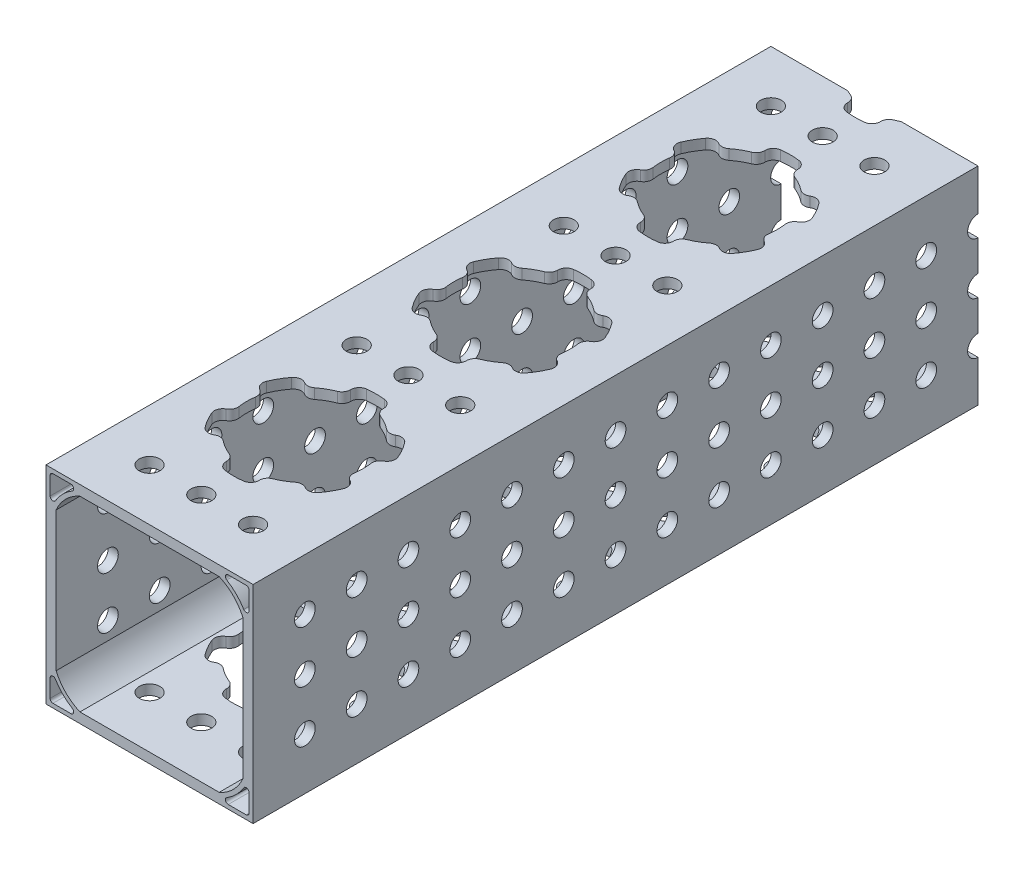
SolidWorks part; units mm, degrees
material "6061 Alloy"
ref_plane "Front Plane" through (0, 0, 0) normal (0, 0, 1) x (1, 0, 0)
ref_plane "Top Plane" through (0, 0, 0) normal (0, 1, 0) x (1, 0, 0)
ref_plane "Right Plane" through (0, 0, 0) normal (1, 0, 0) x (0, 0, -1)
other "Configuration Table"
sketch "Sketch1" plane through (0, 0, 0) normal (0, 0, 1) x (1, 0, 0)
  line L1 (-25.4, -25.4) -> (25.4, -25.4)
  line L2 (-25.4, -25.4) -> (-25.4, 25.4)
  line L3 (-25.4, 25.4) -> (25.4, 25.4)
  line L4 (25.4, -25.4) -> (25.4, 25.4)
  line L5 (-25.4, -25.4) -> (25.4, 25.4) construction
  line L6 (-25.4, 25.4) -> (25.4, -25.4) construction
  point P0 (0, 0)
  dimension "D1" = 50.8
extrude "Boss-Extrude1" add sketch "Sketch1" along normal mid plane 177.8
sketch "Sketch2" plane through (0, 0, 88.9) normal (0, 0, 1) x (1, 0, 0)
  line L10 (0, 0) -> (0, 22.9141)
  line L11 (-22.9141, 0) -> (0, 0)
  line L12 (-22.9141, 17.0772) -> (-22.9141, 0)
  line L13 (0, 22.9141) -> (-17.0772, 22.9141)
  line L14 (-24.384, 23.6924) -> (-24.384, 19.2971)
  line L15 (-19.2971, 24.384) -> (-23.6924, 24.384)
  line L16 (25.4, -25.4) -> (25.4, 25.4) construction
  arc A12 (-17.0772, 22.9141) -> (-22.9141, 17.0772) centre (-12.7, 12.7) ccw
  arc A13 (-18.9412, 23.0994) -> (-23.0994, 18.9412) centre (-12.7, 12.7) ccw
  arc A14 (-24.384, 19.2971) -> (-23.0994, 18.9412) centre (-23.6924, 19.2971) ccw
  arc A15 (-23.6924, 24.384) -> (-24.384, 23.6924) centre (-23.6924, 23.6924) ccw
  arc A16 (-18.6055, 23.6924) -> (-19.2971, 24.384) centre (-19.2971, 23.6924) ccw
  arc A17 (-18.9412, 23.0994) -> (-18.6055, 23.6924) centre (-19.2971, 23.6924) ccw
  dimension "D1" = 11.1125
  dimension "D2" = 12.1285
  dimension "D3" = 0.6916
  dimension "D4" = 12.7
  dimension "D5" = 42.4772
  dimension "D6" = 44.0055
extrude "Cut-Extrude1" cut sketch "Sketch2" against normal through all
mirror "Mirror1" about plane through (0, 0, 0) normal (1, 0, 0) of "Cut-Extrude1" second plane through (0, 0, 0) second plane normal (0, 1, 0)
sketch "Sketch3" plane through (0, 25.4, 0) normal (0, 1, 0) x (1, 0, 0)
  line L0 (25.4, -88.9) -> (-25.4, -88.9) construction
  line L1 (-12.7, -76.2) -> (0, -76.2) construction
  line L2 (0, -76.2) -> (12.7, -76.2) construction
  line L3 (-25.4, -88.9) -> (-25.4, 88.9) construction
  circle A0 centre (-12.7, -76.2) radius 2.54
  circle A1 centre (0, -76.2) radius 2.54
  circle A2 centre (12.7, -76.2) radius 2.54
  arc A3 (-13.8805, -40.2042) -> (-16.1165, -44.077) centre (0, -50.8) ccw
  arc A4 (-11.1752, -39.7031) -> (-13.8805, -40.2042) centre (-12.251, -41.4481) ccw
  arc A5 (-5.3099, -37.5358) -> (-8.8322, -39.5694) centre (0, -50.8) ccw
  arc A6 (-11.1752, -39.7031) -> (-8.8322, -39.5694) centre (-10.0994, -37.958) ccw
  arc A7 (-5.3099, -37.5358) -> (-4.0226, -35.5735) centre (-6.0717, -35.6327) ccw
  arc A8 (-2.2359, -33.4812) -> (-4.0226, -35.5735) centre (-1.9735, -35.5144) ccw
  circle A9 centre (0, -50.8) radius 14.2875 construction
  arc A10 (2.2359, -33.4812) -> (-2.2359, -33.4812) centre (0, -50.8) ccw
  arc A11 (4.0226, -35.5735) -> (2.2359, -33.4812) centre (1.9735, -35.5144) ccw
  arc A12 (4.0226, -35.5735) -> (5.3099, -37.5358) centre (6.0717, -35.6327) ccw
  arc A13 (8.8322, -39.5694) -> (5.3099, -37.5358) centre (0, -50.8) ccw
  arc A14 (8.8322, -39.5694) -> (11.1752, -39.7031) centre (10.0994, -37.958) ccw
  arc A15 (13.8805, -40.2042) -> (11.1752, -39.7031) centre (12.251, -41.4481) ccw
  arc A16 (16.1165, -44.077) -> (13.8805, -40.2042) centre (0, -50.8) ccw
  arc A17 (15.1978, -46.6704) -> (16.1165, -44.077) centre (14.2245, -44.8662) ccw
  arc A18 (15.1978, -46.6704) -> (14.142, -48.7664) centre (16.1712, -48.4746) ccw
  arc A19 (14.142, -52.8336) -> (14.142, -48.7664) centre (0, -50.8) ccw
  arc A20 (14.142, -52.8336) -> (15.1978, -54.9296) centre (16.1712, -53.1254) ccw
  arc A21 (16.1165, -57.523) -> (15.1978, -54.9296) centre (14.2245, -56.7338) ccw
  arc A22 (13.8805, -61.3958) -> (16.1165, -57.523) centre (0, -50.8) ccw
  arc A23 (11.1752, -61.8969) -> (13.8805, -61.3958) centre (12.251, -60.1519) ccw
  arc A24 (11.1752, -61.8969) -> (8.8322, -62.0306) centre (10.0994, -63.642) ccw
  arc A25 (5.3099, -64.0642) -> (8.8322, -62.0306) centre (0, -50.8) ccw
  arc A26 (5.3099, -64.0642) -> (4.0226, -66.0265) centre (6.0717, -65.9673) ccw
  arc A27 (2.2359, -68.1188) -> (4.0226, -66.0265) centre (1.9735, -66.0856) ccw
  arc A28 (-2.2359, -68.1188) -> (2.2359, -68.1188) centre (0, -50.8) ccw
  arc A29 (-4.0226, -66.0265) -> (-2.2359, -68.1188) centre (-1.9735, -66.0856) ccw
  arc A30 (-4.0226, -66.0265) -> (-5.3099, -64.0642) centre (-6.0717, -65.9673) ccw
  arc A31 (-8.8322, -62.0306) -> (-5.3099, -64.0642) centre (0, -50.8) ccw
  arc A32 (-8.8322, -62.0306) -> (-11.1752, -61.8969) centre (-10.0994, -63.642) ccw
  arc A33 (-13.8805, -61.3958) -> (-11.1752, -61.8969) centre (-12.251, -60.1519) ccw
  arc A34 (-16.1165, -57.523) -> (-13.8805, -61.3958) centre (0, -50.8) ccw
  arc A35 (-15.1978, -54.9296) -> (-16.1165, -57.523) centre (-14.2245, -56.7338) ccw
  arc A36 (-15.1978, -54.9296) -> (-14.142, -52.8336) centre (-16.1712, -53.1254) ccw
  arc A37 (-14.142, -48.7664) -> (-14.142, -52.8336) centre (0, -50.8) ccw
  arc A38 (-14.142, -48.7664) -> (-15.1978, -46.6704) centre (-16.1712, -48.4746) ccw
  arc A39 (-16.1165, -44.077) -> (-15.1978, -46.6704) centre (-14.2245, -44.8662) ccw
  arc A40 (-13.8805, 10.5958) -> (-16.1165, 6.723) centre (0, 0) ccw
  arc A41 (-16.1165, 6.723) -> (-15.1978, 4.1296) centre (-14.2245, 5.9338) ccw
  arc A42 (-14.142, 2.0336) -> (-15.1978, 4.1296) centre (-16.1712, 2.3254) ccw
  arc A43 (-14.142, 2.0336) -> (-14.142, -2.0336) centre (0, 0) ccw
  arc A44 (-15.1978, -4.1296) -> (-14.142, -2.0336) centre (-16.1712, -2.3254) ccw
  arc A45 (-15.1978, -4.1296) -> (-16.1165, -6.723) centre (-14.2245, -5.9338) ccw
  arc A46 (-16.1165, -6.723) -> (-13.8805, -10.5958) centre (0, 0) ccw
  arc A47 (-13.8805, -10.5958) -> (-11.1752, -11.0969) centre (-12.251, -9.3519) ccw
  arc A48 (-8.8322, -11.2306) -> (-11.1752, -11.0969) centre (-10.0994, -12.842) ccw
  arc A49 (-8.8322, -11.2306) -> (-5.3099, -13.2642) centre (0, 0) ccw
  arc A50 (-4.0226, -15.2265) -> (-5.3099, -13.2642) centre (-6.0717, -15.1673) ccw
  arc A51 (-4.0226, -15.2265) -> (-2.2359, -17.3188) centre (-1.9735, -15.2856) ccw
  arc A52 (-2.2359, -17.3188) -> (2.2359, -17.3188) centre (0, 0) ccw
  arc A53 (2.2359, -17.3188) -> (4.0226, -15.2265) centre (1.9735, -15.2856) ccw
  arc A54 (5.3099, -13.2642) -> (4.0226, -15.2265) centre (6.0717, -15.1673) ccw
  arc A55 (5.3099, -13.2642) -> (8.8322, -11.2306) centre (0, 0) ccw
  arc A56 (11.1752, -11.0969) -> (8.8322, -11.2306) centre (10.0994, -12.842) ccw
  arc A57 (11.1752, -11.0969) -> (13.8805, -10.5958) centre (12.251, -9.3519) ccw
  arc A58 (13.8805, -10.5958) -> (16.1165, -6.723) centre (0, 0) ccw
  arc A59 (16.1165, -6.723) -> (15.1978, -4.1296) centre (14.2245, -5.9338) ccw
  arc A60 (14.142, -2.0336) -> (15.1978, -4.1296) centre (16.1712, -2.3254) ccw
  arc A61 (14.142, -2.0336) -> (14.142, 2.0336) centre (0, 0) ccw
  arc A62 (15.1978, 4.1296) -> (14.142, 2.0336) centre (16.1712, 2.3254) ccw
  arc A63 (15.1978, 4.1296) -> (16.1165, 6.723) centre (14.2245, 5.9338) ccw
  arc A64 (16.1165, 6.723) -> (13.8805, 10.5958) centre (0, 0) ccw
  arc A65 (13.8805, 10.5958) -> (11.1752, 11.0969) centre (12.251, 9.3519) ccw
  arc A66 (8.8322, 11.2306) -> (11.1752, 11.0969) centre (10.0994, 12.842) ccw
  arc A67 (8.8322, 11.2306) -> (5.3099, 13.2642) centre (0, 0) ccw
  arc A68 (4.0226, 15.2265) -> (5.3099, 13.2642) centre (6.0717, 15.1673) ccw
  arc A69 (4.0226, 15.2265) -> (2.2359, 17.3188) centre (1.9735, 15.2856) ccw
  arc A70 (2.2359, 17.3188) -> (-2.2359, 17.3188) centre (0, 0) ccw
  arc A71 (-2.2359, 17.3188) -> (-4.0226, 15.2265) centre (-1.9735, 15.2856) ccw
  arc A72 (-5.3099, 13.2642) -> (-4.0226, 15.2265) centre (-6.0717, 15.1673) ccw
  arc A73 (-5.3099, 13.2642) -> (-8.8322, 11.2306) centre (0, 0) ccw
  arc A74 (-11.1752, 11.0969) -> (-8.8322, 11.2306) centre (-10.0994, 12.842) ccw
  arc A75 (-11.1752, 11.0969) -> (-13.8805, 10.5958) centre (-12.251, 9.3519) ccw
  circle A76 centre (-12.7, -25.4) radius 2.54
  circle A77 centre (0, -25.4) radius 2.54
  circle A78 centre (12.7, -25.4) radius 2.54
  arc A79 (-13.8805, 61.3958) -> (-16.1165, 57.523) centre (0, 50.8) ccw
  arc A80 (-16.1165, 57.523) -> (-15.1978, 54.9296) centre (-14.2245, 56.7338) ccw
  arc A81 (-14.142, 52.8336) -> (-15.1978, 54.9296) centre (-16.1712, 53.1254) ccw
  arc A82 (-14.142, 52.8336) -> (-14.142, 48.7664) centre (0, 50.8) ccw
  arc A83 (-15.1978, 46.6704) -> (-14.142, 48.7664) centre (-16.1712, 48.4746) ccw
  arc A84 (-15.1978, 46.6704) -> (-16.1165, 44.077) centre (-14.2245, 44.8662) ccw
  arc A85 (-16.1165, 44.077) -> (-13.8805, 40.2042) centre (0, 50.8) ccw
  arc A86 (-13.8805, 40.2042) -> (-11.1752, 39.7031) centre (-12.251, 41.4481) ccw
  arc A87 (-8.8322, 39.5694) -> (-11.1752, 39.7031) centre (-10.0994, 37.958) ccw
  arc A88 (-8.8322, 39.5694) -> (-5.3099, 37.5358) centre (0, 50.8) ccw
  arc A89 (-4.0226, 35.5735) -> (-5.3099, 37.5358) centre (-6.0717, 35.6327) ccw
  arc A90 (-4.0226, 35.5735) -> (-2.2359, 33.4812) centre (-1.9735, 35.5144) ccw
  arc A91 (-2.2359, 33.4812) -> (2.2359, 33.4812) centre (0, 50.8) ccw
  arc A92 (2.2359, 33.4812) -> (4.0226, 35.5735) centre (1.9735, 35.5144) ccw
  arc A93 (5.3099, 37.5358) -> (4.0226, 35.5735) centre (6.0717, 35.6327) ccw
  arc A94 (5.3099, 37.5358) -> (8.8322, 39.5694) centre (0, 50.8) ccw
  arc A95 (11.1752, 39.7031) -> (8.8322, 39.5694) centre (10.0994, 37.958) ccw
  arc A96 (11.1752, 39.7031) -> (13.8805, 40.2042) centre (12.251, 41.4481) ccw
  arc A97 (13.8805, 40.2042) -> (16.1165, 44.077) centre (0, 50.8) ccw
  arc A98 (16.1165, 44.077) -> (15.1978, 46.6704) centre (14.2245, 44.8662) ccw
  arc A99 (14.142, 48.7664) -> (15.1978, 46.6704) centre (16.1712, 48.4746) ccw
  arc A100 (14.142, 48.7664) -> (14.142, 52.8336) centre (0, 50.8) ccw
  arc A101 (15.1978, 54.9296) -> (14.142, 52.8336) centre (16.1712, 53.1254) ccw
  arc A102 (15.1978, 54.9296) -> (16.1165, 57.523) centre (14.2245, 56.7338) ccw
  arc A103 (16.1165, 57.523) -> (13.8805, 61.3958) centre (0, 50.8) ccw
  arc A104 (13.8805, 61.3958) -> (11.1752, 61.8969) centre (12.251, 60.1519) ccw
  arc A105 (8.8322, 62.0306) -> (11.1752, 61.8969) centre (10.0994, 63.642) ccw
  arc A106 (8.8322, 62.0306) -> (5.3099, 64.0642) centre (0, 50.8) ccw
  arc A107 (4.0226, 66.0265) -> (5.3099, 64.0642) centre (6.0717, 65.9673) ccw
  arc A108 (4.0226, 66.0265) -> (2.2359, 68.1188) centre (1.9735, 66.0856) ccw
  arc A109 (2.2359, 68.1188) -> (-2.2359, 68.1188) centre (0, 50.8) ccw
  arc A110 (-2.2359, 68.1188) -> (-4.0226, 66.0265) centre (-1.9735, 66.0856) ccw
  arc A111 (-5.3099, 64.0642) -> (-4.0226, 66.0265) centre (-6.0717, 65.9673) ccw
  arc A112 (-5.3099, 64.0642) -> (-8.8322, 62.0306) centre (0, 50.8) ccw
  arc A113 (-11.1752, 61.8969) -> (-8.8322, 62.0306) centre (-10.0994, 63.642) ccw
  arc A114 (-11.1752, 61.8969) -> (-13.8805, 61.3958) centre (-12.251, 60.1519) ccw
  circle A115 centre (-12.7, 25.4) radius 2.54
  circle A116 centre (0, 25.4) radius 2.54
  circle A117 centre (12.7, 25.4) radius 2.54
  arc A118 (-13.8805, 112.1958) -> (-16.1165, 108.323) centre (0, 101.6) ccw
  arc A119 (-16.1165, 108.323) -> (-15.1978, 105.7296) centre (-14.2245, 107.5338) ccw
  arc A120 (-14.142, 103.6336) -> (-15.1978, 105.7296) centre (-16.1712, 103.9254) ccw
  arc A121 (-14.142, 103.6336) -> (-14.142, 99.5664) centre (0, 101.6) ccw
  arc A122 (-15.1978, 97.4704) -> (-14.142, 99.5664) centre (-16.1712, 99.2746) ccw
  arc A123 (-15.1978, 97.4704) -> (-16.1165, 94.877) centre (-14.2245, 95.6662) ccw
  arc A124 (-16.1165, 94.877) -> (-13.8805, 91.0042) centre (0, 101.6) ccw
  arc A125 (-13.8805, 91.0042) -> (-11.1752, 90.5031) centre (-12.251, 92.2481) ccw
  arc A126 (-8.8322, 90.3694) -> (-11.1752, 90.5031) centre (-10.0994, 88.758) ccw
  arc A127 (-8.8322, 90.3694) -> (-5.3099, 88.3358) centre (0, 101.6) ccw
  arc A128 (-4.0226, 86.3735) -> (-5.3099, 88.3358) centre (-6.0717, 86.4327) ccw
  arc A129 (-4.0226, 86.3735) -> (-2.2359, 84.2812) centre (-1.9735, 86.3144) ccw
  arc A130 (-2.2359, 84.2812) -> (2.2359, 84.2812) centre (0, 101.6) ccw
  arc A131 (2.2359, 84.2812) -> (4.0226, 86.3735) centre (1.9735, 86.3144) ccw
  arc A132 (5.3099, 88.3358) -> (4.0226, 86.3735) centre (6.0717, 86.4327) ccw
  arc A133 (5.3099, 88.3358) -> (8.8322, 90.3694) centre (0, 101.6) ccw
  arc A134 (11.1752, 90.5031) -> (8.8322, 90.3694) centre (10.0994, 88.758) ccw
  arc A135 (11.1752, 90.5031) -> (13.8805, 91.0042) centre (12.251, 92.2481) ccw
  arc A136 (13.8805, 91.0042) -> (16.1165, 94.877) centre (0, 101.6) ccw
  arc A137 (16.1165, 94.877) -> (15.1978, 97.4704) centre (14.2245, 95.6662) ccw
  arc A138 (14.142, 99.5664) -> (15.1978, 97.4704) centre (16.1712, 99.2746) ccw
  arc A139 (14.142, 99.5664) -> (14.142, 103.6336) centre (0, 101.6) ccw
  arc A140 (15.1978, 105.7296) -> (14.142, 103.6336) centre (16.1712, 103.9254) ccw
  arc A141 (15.1978, 105.7296) -> (16.1165, 108.323) centre (14.2245, 107.5338) ccw
  arc A142 (16.1165, 108.323) -> (13.8805, 112.1958) centre (0, 101.6) ccw
  arc A143 (13.8805, 112.1958) -> (11.1752, 112.6969) centre (12.251, 110.9519) ccw
  arc A144 (8.8322, 112.8306) -> (11.1752, 112.6969) centre (10.0994, 114.442) ccw
  arc A145 (8.8322, 112.8306) -> (5.3099, 114.8642) centre (0, 101.6) ccw
  arc A146 (4.0226, 116.8265) -> (5.3099, 114.8642) centre (6.0717, 116.7673) ccw
  arc A147 (4.0226, 116.8265) -> (2.2359, 118.9188) centre (1.9735, 116.8856) ccw
  arc A148 (2.2359, 118.9188) -> (-2.2359, 118.9188) centre (0, 101.6) ccw
  arc A149 (-2.2359, 118.9188) -> (-4.0226, 116.8265) centre (-1.9735, 116.8856) ccw
  arc A150 (-5.3099, 114.8642) -> (-4.0226, 116.8265) centre (-6.0717, 116.7673) ccw
  arc A151 (-5.3099, 114.8642) -> (-8.8322, 112.8306) centre (0, 101.6) ccw
  arc A152 (-11.1752, 112.6969) -> (-8.8322, 112.8306) centre (-10.0994, 114.442) ccw
  arc A153 (-11.1752, 112.6969) -> (-13.8805, 112.1958) centre (-12.251, 110.9519) ccw
  circle A154 centre (-12.7, 76.2) radius 2.54
  circle A155 centre (0, 76.2) radius 2.54
  circle A156 centre (12.7, 76.2) radius 2.54
  arc A157 (-13.8805, 162.9958) -> (-16.1165, 159.123) centre (0, 152.4) ccw
  arc A158 (-16.1165, 159.123) -> (-15.1978, 156.5296) centre (-14.2245, 158.3338) ccw
  arc A159 (-14.142, 154.4336) -> (-15.1978, 156.5296) centre (-16.1712, 154.7254) ccw
  arc A160 (-14.142, 154.4336) -> (-14.142, 150.3664) centre (0, 152.4) ccw
  arc A161 (-15.1978, 148.2704) -> (-14.142, 150.3664) centre (-16.1712, 150.0746) ccw
  arc A162 (-15.1978, 148.2704) -> (-16.1165, 145.677) centre (-14.2245, 146.4662) ccw
  arc A163 (-16.1165, 145.677) -> (-13.8805, 141.8042) centre (0, 152.4) ccw
  arc A164 (-13.8805, 141.8042) -> (-11.1752, 141.3031) centre (-12.251, 143.0481) ccw
  arc A165 (-8.8322, 141.1694) -> (-11.1752, 141.3031) centre (-10.0994, 139.558) ccw
  arc A166 (-8.8322, 141.1694) -> (-5.3099, 139.1358) centre (0, 152.4) ccw
  arc A167 (-4.0226, 137.1735) -> (-5.3099, 139.1358) centre (-6.0717, 137.2327) ccw
  arc A168 (-4.0226, 137.1735) -> (-2.2359, 135.0812) centre (-1.9735, 137.1144) ccw
  arc A169 (-2.2359, 135.0812) -> (2.2359, 135.0812) centre (0, 152.4) ccw
  arc A170 (2.2359, 135.0812) -> (4.0226, 137.1735) centre (1.9735, 137.1144) ccw
  arc A171 (5.3099, 139.1358) -> (4.0226, 137.1735) centre (6.0717, 137.2327) ccw
  arc A172 (5.3099, 139.1358) -> (8.8322, 141.1694) centre (0, 152.4) ccw
  arc A173 (11.1752, 141.3031) -> (8.8322, 141.1694) centre (10.0994, 139.558) ccw
  arc A174 (11.1752, 141.3031) -> (13.8805, 141.8042) centre (12.251, 143.0481) ccw
  arc A175 (13.8805, 141.8042) -> (16.1165, 145.677) centre (0, 152.4) ccw
  arc A176 (16.1165, 145.677) -> (15.1978, 148.2704) centre (14.2245, 146.4662) ccw
  arc A177 (14.142, 150.3664) -> (15.1978, 148.2704) centre (16.1712, 150.0746) ccw
  arc A178 (14.142, 150.3664) -> (14.142, 154.4336) centre (0, 152.4) ccw
  arc A179 (15.1978, 156.5296) -> (14.142, 154.4336) centre (16.1712, 154.7254) ccw
  arc A180 (15.1978, 156.5296) -> (16.1165, 159.123) centre (14.2245, 158.3338) ccw
  arc A181 (16.1165, 159.123) -> (13.8805, 162.9958) centre (0, 152.4) ccw
  arc A182 (13.8805, 162.9958) -> (11.1752, 163.4969) centre (12.251, 161.7519) ccw
  arc A183 (8.8322, 163.6306) -> (11.1752, 163.4969) centre (10.0994, 165.242) ccw
  arc A184 (8.8322, 163.6306) -> (5.3099, 165.6642) centre (0, 152.4) ccw
  arc A185 (4.0226, 167.6265) -> (5.3099, 165.6642) centre (6.0717, 167.5673) ccw
  arc A186 (4.0226, 167.6265) -> (2.2359, 169.7188) centre (1.9735, 167.6856) ccw
  arc A187 (2.2359, 169.7188) -> (-2.2359, 169.7188) centre (0, 152.4) ccw
  arc A188 (-2.2359, 169.7188) -> (-4.0226, 167.6265) centre (-1.9735, 167.6856) ccw
  arc A189 (-5.3099, 165.6642) -> (-4.0226, 167.6265) centre (-6.0717, 167.5673) ccw
  arc A190 (-5.3099, 165.6642) -> (-8.8322, 163.6306) centre (0, 152.4) ccw
  arc A191 (-11.1752, 163.4969) -> (-8.8322, 163.6306) centre (-10.0994, 165.242) ccw
  arc A192 (-11.1752, 163.4969) -> (-13.8805, 162.9958) centre (-12.251, 161.7519) ccw
  circle A193 centre (-12.7, 127) radius 2.54
  circle A194 centre (0, 127) radius 2.54
  circle A195 centre (12.7, 127) radius 2.54
  arc A196 (-13.8805, 213.7958) -> (-16.1165, 209.923) centre (0, 203.2) ccw
  arc A197 (-16.1165, 209.923) -> (-15.1978, 207.3296) centre (-14.2245, 209.1338) ccw
  arc A198 (-14.142, 205.2336) -> (-15.1978, 207.3296) centre (-16.1712, 205.5254) ccw
  arc A199 (-14.142, 205.2336) -> (-14.142, 201.1664) centre (0, 203.2) ccw
  arc A200 (-15.1978, 199.0704) -> (-14.142, 201.1664) centre (-16.1712, 200.8746) ccw
  arc A201 (-15.1978, 199.0704) -> (-16.1165, 196.477) centre (-14.2245, 197.2662) ccw
  arc A202 (-16.1165, 196.477) -> (-13.8805, 192.6042) centre (0, 203.2) ccw
  arc A203 (-13.8805, 192.6042) -> (-11.1752, 192.1031) centre (-12.251, 193.8481) ccw
  arc A204 (-8.8322, 191.9694) -> (-11.1752, 192.1031) centre (-10.0994, 190.358) ccw
  arc A205 (-8.8322, 191.9694) -> (-5.3099, 189.9358) centre (0, 203.2) ccw
  arc A206 (-4.0226, 187.9735) -> (-5.3099, 189.9358) centre (-6.0717, 188.0327) ccw
  arc A207 (-4.0226, 187.9735) -> (-2.2359, 185.8812) centre (-1.9735, 187.9144) ccw
  arc A208 (-2.2359, 185.8812) -> (2.2359, 185.8812) centre (0, 203.2) ccw
  arc A209 (2.2359, 185.8812) -> (4.0226, 187.9735) centre (1.9735, 187.9144) ccw
  arc A210 (5.3099, 189.9358) -> (4.0226, 187.9735) centre (6.0717, 188.0327) ccw
  arc A211 (5.3099, 189.9358) -> (8.8322, 191.9694) centre (0, 203.2) ccw
  arc A212 (11.1752, 192.1031) -> (8.8322, 191.9694) centre (10.0994, 190.358) ccw
  arc A213 (11.1752, 192.1031) -> (13.8805, 192.6042) centre (12.251, 193.8481) ccw
  arc A214 (13.8805, 192.6042) -> (16.1165, 196.477) centre (0, 203.2) ccw
  arc A215 (16.1165, 196.477) -> (15.1978, 199.0704) centre (14.2245, 197.2662) ccw
  arc A216 (14.142, 201.1664) -> (15.1978, 199.0704) centre (16.1712, 200.8746) ccw
  arc A217 (14.142, 201.1664) -> (14.142, 205.2336) centre (0, 203.2) ccw
  arc A218 (15.1978, 207.3296) -> (14.142, 205.2336) centre (16.1712, 205.5254) ccw
  arc A219 (15.1978, 207.3296) -> (16.1165, 209.923) centre (14.2245, 209.1338) ccw
  arc A220 (16.1165, 209.923) -> (13.8805, 213.7958) centre (0, 203.2) ccw
  arc A221 (13.8805, 213.7958) -> (11.1752, 214.2969) centre (12.251, 212.5519) ccw
  arc A222 (8.8322, 214.4306) -> (11.1752, 214.2969) centre (10.0994, 216.042) ccw
  arc A223 (8.8322, 214.4306) -> (5.3099, 216.4642) centre (0, 203.2) ccw
  arc A224 (4.0226, 218.4265) -> (5.3099, 216.4642) centre (6.0717, 218.3673) ccw
  arc A225 (4.0226, 218.4265) -> (2.2359, 220.5188) centre (1.9735, 218.4856) ccw
  arc A226 (2.2359, 220.5188) -> (-2.2359, 220.5188) centre (0, 203.2) ccw
  arc A227 (-2.2359, 220.5188) -> (-4.0226, 218.4265) centre (-1.9735, 218.4856) ccw
  arc A228 (-5.3099, 216.4642) -> (-4.0226, 218.4265) centre (-6.0717, 218.3673) ccw
  arc A229 (-5.3099, 216.4642) -> (-8.8322, 214.4306) centre (0, 203.2) ccw
  arc A230 (-11.1752, 214.2969) -> (-8.8322, 214.4306) centre (-10.0994, 216.042) ccw
  arc A231 (-11.1752, 214.2969) -> (-13.8805, 213.7958) centre (-12.251, 212.5519) ccw
  circle A232 centre (-12.7, 177.8) radius 2.54
  circle A233 centre (0, 177.8) radius 2.54
  circle A234 centre (12.7, 177.8) radius 2.54
  arc A235 (-13.8805, 264.5958) -> (-16.1165, 260.723) centre (0, 254) ccw
  arc A236 (-16.1165, 260.723) -> (-15.1978, 258.1296) centre (-14.2245, 259.9338) ccw
  arc A237 (-14.142, 256.0336) -> (-15.1978, 258.1296) centre (-16.1712, 256.3254) ccw
  arc A238 (-14.142, 256.0336) -> (-14.142, 251.9664) centre (0, 254) ccw
  arc A239 (-15.1978, 249.8704) -> (-14.142, 251.9664) centre (-16.1712, 251.6746) ccw
  arc A240 (-15.1978, 249.8704) -> (-16.1165, 247.277) centre (-14.2245, 248.0662) ccw
  arc A241 (-16.1165, 247.277) -> (-13.8805, 243.4042) centre (0, 254) ccw
  arc A242 (-13.8805, 243.4042) -> (-11.1752, 242.9031) centre (-12.251, 244.6481) ccw
  arc A243 (-8.8322, 242.7694) -> (-11.1752, 242.9031) centre (-10.0994, 241.158) ccw
  arc A244 (-8.8322, 242.7694) -> (-5.3099, 240.7358) centre (0, 254) ccw
  arc A245 (-4.0226, 238.7735) -> (-5.3099, 240.7358) centre (-6.0717, 238.8327) ccw
  arc A246 (-4.0226, 238.7735) -> (-2.2359, 236.6812) centre (-1.9735, 238.7144) ccw
  arc A247 (-2.2359, 236.6812) -> (2.2359, 236.6812) centre (0, 254) ccw
  arc A248 (2.2359, 236.6812) -> (4.0226, 238.7735) centre (1.9735, 238.7144) ccw
  arc A249 (5.3099, 240.7358) -> (4.0226, 238.7735) centre (6.0717, 238.8327) ccw
  arc A250 (5.3099, 240.7358) -> (8.8322, 242.7694) centre (0, 254) ccw
  arc A251 (11.1752, 242.9031) -> (8.8322, 242.7694) centre (10.0994, 241.158) ccw
  arc A252 (11.1752, 242.9031) -> (13.8805, 243.4042) centre (12.251, 244.6481) ccw
  arc A253 (13.8805, 243.4042) -> (16.1165, 247.277) centre (0, 254) ccw
  arc A254 (16.1165, 247.277) -> (15.1978, 249.8704) centre (14.2245, 248.0662) ccw
  arc A255 (14.142, 251.9664) -> (15.1978, 249.8704) centre (16.1712, 251.6746) ccw
  arc A256 (14.142, 251.9664) -> (14.142, 256.0336) centre (0, 254) ccw
  arc A257 (15.1978, 258.1296) -> (14.142, 256.0336) centre (16.1712, 256.3254) ccw
  arc A258 (15.1978, 258.1296) -> (16.1165, 260.723) centre (14.2245, 259.9338) ccw
  arc A259 (16.1165, 260.723) -> (13.8805, 264.5958) centre (0, 254) ccw
  arc A260 (13.8805, 264.5958) -> (11.1752, 265.0969) centre (12.251, 263.3519) ccw
  arc A261 (8.8322, 265.2306) -> (11.1752, 265.0969) centre (10.0994, 266.842) ccw
  arc A262 (8.8322, 265.2306) -> (5.3099, 267.2642) centre (0, 254) ccw
  arc A263 (4.0226, 269.2265) -> (5.3099, 267.2642) centre (6.0717, 269.1673) ccw
  arc A264 (4.0226, 269.2265) -> (2.2359, 271.3188) centre (1.9735, 269.2856) ccw
  arc A265 (2.2359, 271.3188) -> (-2.2359, 271.3188) centre (0, 254) ccw
  arc A266 (-2.2359, 271.3188) -> (-4.0226, 269.2265) centre (-1.9735, 269.2856) ccw
  arc A267 (-5.3099, 267.2642) -> (-4.0226, 269.2265) centre (-6.0717, 269.1673) ccw
  arc A268 (-5.3099, 267.2642) -> (-8.8322, 265.2306) centre (0, 254) ccw
  arc A269 (-11.1752, 265.0969) -> (-8.8322, 265.2306) centre (-10.0994, 266.842) ccw
  arc A270 (-11.1752, 265.0969) -> (-13.8805, 264.5958) centre (-12.251, 263.3519) ccw
  circle A271 centre (-12.7, 228.6) radius 2.54
  circle A272 centre (0, 228.6) radius 2.54
  circle A273 centre (12.7, 228.6) radius 2.54
  arc A274 (-13.8805, 315.3958) -> (-16.1165, 311.523) centre (0, 304.8) ccw
  arc A275 (-16.1165, 311.523) -> (-15.1978, 308.9296) centre (-14.2245, 310.7338) ccw
  arc A276 (-14.142, 306.8336) -> (-15.1978, 308.9296) centre (-16.1712, 307.1254) ccw
  arc A277 (-14.142, 306.8336) -> (-14.142, 302.7664) centre (0, 304.8) ccw
  arc A278 (-15.1978, 300.6704) -> (-14.142, 302.7664) centre (-16.1712, 302.4746) ccw
  arc A279 (-15.1978, 300.6704) -> (-16.1165, 298.077) centre (-14.2245, 298.8662) ccw
  arc A280 (-16.1165, 298.077) -> (-13.8805, 294.2042) centre (0, 304.8) ccw
  arc A281 (-13.8805, 294.2042) -> (-11.1752, 293.7031) centre (-12.251, 295.4481) ccw
  arc A282 (-8.8322, 293.5694) -> (-11.1752, 293.7031) centre (-10.0994, 291.958) ccw
  arc A283 (-8.8322, 293.5694) -> (-5.3099, 291.5358) centre (0, 304.8) ccw
  arc A284 (-4.0226, 289.5735) -> (-5.3099, 291.5358) centre (-6.0717, 289.6327) ccw
  arc A285 (-4.0226, 289.5735) -> (-2.2359, 287.4812) centre (-1.9735, 289.5144) ccw
  arc A286 (-2.2359, 287.4812) -> (2.2359, 287.4812) centre (0, 304.8) ccw
  arc A287 (2.2359, 287.4812) -> (4.0226, 289.5735) centre (1.9735, 289.5144) ccw
  arc A288 (5.3099, 291.5358) -> (4.0226, 289.5735) centre (6.0717, 289.6327) ccw
  arc A289 (5.3099, 291.5358) -> (8.8322, 293.5694) centre (0, 304.8) ccw
  arc A290 (11.1752, 293.7031) -> (8.8322, 293.5694) centre (10.0994, 291.958) ccw
  arc A291 (11.1752, 293.7031) -> (13.8805, 294.2042) centre (12.251, 295.4481) ccw
  arc A292 (13.8805, 294.2042) -> (16.1165, 298.077) centre (0, 304.8) ccw
  arc A293 (16.1165, 298.077) -> (15.1978, 300.6704) centre (14.2245, 298.8662) ccw
  arc A294 (14.142, 302.7664) -> (15.1978, 300.6704) centre (16.1712, 302.4746) ccw
  arc A295 (14.142, 302.7664) -> (14.142, 306.8336) centre (0, 304.8) ccw
  arc A296 (15.1978, 308.9296) -> (14.142, 306.8336) centre (16.1712, 307.1254) ccw
  arc A297 (15.1978, 308.9296) -> (16.1165, 311.523) centre (14.2245, 310.7338) ccw
  arc A298 (16.1165, 311.523) -> (13.8805, 315.3958) centre (0, 304.8) ccw
  arc A299 (13.8805, 315.3958) -> (11.1752, 315.8969) centre (12.251, 314.1519) ccw
  arc A300 (8.8322, 316.0306) -> (11.1752, 315.8969) centre (10.0994, 317.642) ccw
  arc A301 (8.8322, 316.0306) -> (5.3099, 318.0642) centre (0, 304.8) ccw
  arc A302 (4.0226, 320.0265) -> (5.3099, 318.0642) centre (6.0717, 319.9673) ccw
  arc A303 (4.0226, 320.0265) -> (2.2359, 322.1188) centre (1.9735, 320.0856) ccw
  arc A304 (2.2359, 322.1188) -> (-2.2359, 322.1188) centre (0, 304.8) ccw
  arc A305 (-2.2359, 322.1188) -> (-4.0226, 320.0265) centre (-1.9735, 320.0856) ccw
  arc A306 (-5.3099, 318.0642) -> (-4.0226, 320.0265) centre (-6.0717, 319.9673) ccw
  arc A307 (-5.3099, 318.0642) -> (-8.8322, 316.0306) centre (0, 304.8) ccw
  arc A308 (-11.1752, 315.8969) -> (-8.8322, 316.0306) centre (-10.0994, 317.642) ccw
  arc A309 (-11.1752, 315.8969) -> (-13.8805, 315.3958) centre (-12.251, 314.1519) ccw
  circle A310 centre (-12.7, 279.4) radius 2.54
  circle A311 centre (0, 279.4) radius 2.54
  circle A312 centre (12.7, 279.4) radius 2.54
  arc A313 (-13.8805, 366.1958) -> (-16.1165, 362.323) centre (0, 355.6) ccw
  arc A314 (-16.1165, 362.323) -> (-15.1978, 359.7296) centre (-14.2245, 361.5338) ccw
  arc A315 (-14.142, 357.6336) -> (-15.1978, 359.7296) centre (-16.1712, 357.9254) ccw
  arc A316 (-14.142, 357.6336) -> (-14.142, 353.5664) centre (0, 355.6) ccw
  arc A317 (-15.1978, 351.4704) -> (-14.142, 353.5664) centre (-16.1712, 353.2746) ccw
  arc A318 (-15.1978, 351.4704) -> (-16.1165, 348.877) centre (-14.2245, 349.6662) ccw
  arc A319 (-16.1165, 348.877) -> (-13.8805, 345.0042) centre (0, 355.6) ccw
  arc A320 (-13.8805, 345.0042) -> (-11.1752, 344.5031) centre (-12.251, 346.2481) ccw
  arc A321 (-8.8322, 344.3694) -> (-11.1752, 344.5031) centre (-10.0994, 342.758) ccw
  arc A322 (-8.8322, 344.3694) -> (-5.3099, 342.3358) centre (0, 355.6) ccw
  arc A323 (-4.0226, 340.3735) -> (-5.3099, 342.3358) centre (-6.0717, 340.4327) ccw
  arc A324 (-4.0226, 340.3735) -> (-2.2359, 338.2812) centre (-1.9735, 340.3144) ccw
  arc A325 (-2.2359, 338.2812) -> (2.2359, 338.2812) centre (0, 355.6) ccw
  arc A326 (2.2359, 338.2812) -> (4.0226, 340.3735) centre (1.9735, 340.3144) ccw
  arc A327 (5.3099, 342.3358) -> (4.0226, 340.3735) centre (6.0717, 340.4327) ccw
  arc A328 (5.3099, 342.3358) -> (8.8322, 344.3694) centre (0, 355.6) ccw
  arc A329 (11.1752, 344.5031) -> (8.8322, 344.3694) centre (10.0994, 342.758) ccw
  arc A330 (11.1752, 344.5031) -> (13.8805, 345.0042) centre (12.251, 346.2481) ccw
  arc A331 (13.8805, 345.0042) -> (16.1165, 348.877) centre (0, 355.6) ccw
  arc A332 (16.1165, 348.877) -> (15.1978, 351.4704) centre (14.2245, 349.6662) ccw
  arc A333 (14.142, 353.5664) -> (15.1978, 351.4704) centre (16.1712, 353.2746) ccw
  arc A334 (14.142, 353.5664) -> (14.142, 357.6336) centre (0, 355.6) ccw
  arc A335 (15.1978, 359.7296) -> (14.142, 357.6336) centre (16.1712, 357.9254) ccw
  arc A336 (15.1978, 359.7296) -> (16.1165, 362.323) centre (14.2245, 361.5338) ccw
  arc A337 (16.1165, 362.323) -> (13.8805, 366.1958) centre (0, 355.6) ccw
  arc A338 (13.8805, 366.1958) -> (11.1752, 366.6969) centre (12.251, 364.9519) ccw
  arc A339 (8.8322, 366.8306) -> (11.1752, 366.6969) centre (10.0994, 368.442) ccw
  arc A340 (8.8322, 366.8306) -> (5.3099, 368.8642) centre (0, 355.6) ccw
  arc A341 (4.0226, 370.8265) -> (5.3099, 368.8642) centre (6.0717, 370.7673) ccw
  arc A342 (4.0226, 370.8265) -> (2.2359, 372.9188) centre (1.9735, 370.8856) ccw
  arc A343 (2.2359, 372.9188) -> (-2.2359, 372.9188) centre (0, 355.6) ccw
  arc A344 (-2.2359, 372.9188) -> (-4.0226, 370.8265) centre (-1.9735, 370.8856) ccw
  arc A345 (-5.3099, 368.8642) -> (-4.0226, 370.8265) centre (-6.0717, 370.7673) ccw
  arc A346 (-5.3099, 368.8642) -> (-8.8322, 366.8306) centre (0, 355.6) ccw
  arc A347 (-11.1752, 366.6969) -> (-8.8322, 366.8306) centre (-10.0994, 368.442) ccw
  arc A348 (-11.1752, 366.6969) -> (-13.8805, 366.1958) centre (-12.251, 364.9519) ccw
  circle A349 centre (-12.7, 330.2) radius 2.54
  circle A350 centre (0, 330.2) radius 2.54
  circle A351 centre (12.7, 330.2) radius 2.54
  arc A352 (-13.8805, 416.9958) -> (-16.1165, 413.123) centre (0, 406.4) ccw
  arc A353 (-16.1165, 413.123) -> (-15.1978, 410.5296) centre (-14.2245, 412.3338) ccw
  arc A354 (-14.142, 408.4336) -> (-15.1978, 410.5296) centre (-16.1712, 408.7254) ccw
  arc A355 (-14.142, 408.4336) -> (-14.142, 404.3664) centre (0, 406.4) ccw
  arc A356 (-15.1978, 402.2704) -> (-14.142, 404.3664) centre (-16.1712, 404.0746) ccw
  arc A357 (-15.1978, 402.2704) -> (-16.1165, 399.677) centre (-14.2245, 400.4662) ccw
  arc A358 (-16.1165, 399.677) -> (-13.8805, 395.8042) centre (0, 406.4) ccw
  arc A359 (-13.8805, 395.8042) -> (-11.1752, 395.3031) centre (-12.251, 397.0481) ccw
  arc A360 (-8.8322, 395.1694) -> (-11.1752, 395.3031) centre (-10.0994, 393.558) ccw
  arc A361 (-8.8322, 395.1694) -> (-5.3099, 393.1358) centre (0, 406.4) ccw
  arc A362 (-4.0226, 391.1735) -> (-5.3099, 393.1358) centre (-6.0717, 391.2327) ccw
  arc A363 (-4.0226, 391.1735) -> (-2.2359, 389.0812) centre (-1.9735, 391.1144) ccw
  arc A364 (-2.2359, 389.0812) -> (2.2359, 389.0812) centre (0, 406.4) ccw
  arc A365 (2.2359, 389.0812) -> (4.0226, 391.1735) centre (1.9735, 391.1144) ccw
  arc A366 (5.3099, 393.1358) -> (4.0226, 391.1735) centre (6.0717, 391.2327) ccw
  arc A367 (5.3099, 393.1358) -> (8.8322, 395.1694) centre (0, 406.4) ccw
  arc A368 (11.1752, 395.3031) -> (8.8322, 395.1694) centre (10.0994, 393.558) ccw
  arc A369 (11.1752, 395.3031) -> (13.8805, 395.8042) centre (12.251, 397.0481) ccw
  arc A370 (13.8805, 395.8042) -> (16.1165, 399.677) centre (0, 406.4) ccw
  arc A371 (16.1165, 399.677) -> (15.1978, 402.2704) centre (14.2245, 400.4662) ccw
  arc A372 (14.142, 404.3664) -> (15.1978, 402.2704) centre (16.1712, 404.0746) ccw
  arc A373 (14.142, 404.3664) -> (14.142, 408.4336) centre (0, 406.4) ccw
  arc A374 (15.1978, 410.5296) -> (14.142, 408.4336) centre (16.1712, 408.7254) ccw
  arc A375 (15.1978, 410.5296) -> (16.1165, 413.123) centre (14.2245, 412.3338) ccw
  arc A376 (16.1165, 413.123) -> (13.8805, 416.9958) centre (0, 406.4) ccw
  arc A377 (13.8805, 416.9958) -> (11.1752, 417.4969) centre (12.251, 415.7519) ccw
  arc A378 (8.8322, 417.6306) -> (11.1752, 417.4969) centre (10.0994, 419.242) ccw
  arc A379 (8.8322, 417.6306) -> (5.3099, 419.6642) centre (0, 406.4) ccw
  arc A380 (4.0226, 421.6265) -> (5.3099, 419.6642) centre (6.0717, 421.5673) ccw
  arc A381 (4.0226, 421.6265) -> (2.2359, 423.7188) centre (1.9735, 421.6856) ccw
  arc A382 (2.2359, 423.7188) -> (-2.2359, 423.7188) centre (0, 406.4) ccw
  arc A383 (-2.2359, 423.7188) -> (-4.0226, 421.6265) centre (-1.9735, 421.6856) ccw
  arc A384 (-5.3099, 419.6642) -> (-4.0226, 421.6265) centre (-6.0717, 421.5673) ccw
  arc A385 (-5.3099, 419.6642) -> (-8.8322, 417.6306) centre (0, 406.4) ccw
  arc A386 (-11.1752, 417.4969) -> (-8.8322, 417.6306) centre (-10.0994, 419.242) ccw
  arc A387 (-11.1752, 417.4969) -> (-13.8805, 416.9958) centre (-12.251, 415.7519) ccw
  circle A388 centre (-12.7, 381) radius 2.54
  circle A389 centre (0, 381) radius 2.54
  circle A390 centre (12.7, 381) radius 2.54
  arc A391 (-13.8805, 467.7958) -> (-16.1165, 463.923) centre (0, 457.2) ccw
  arc A392 (-16.1165, 463.923) -> (-15.1978, 461.3296) centre (-14.2245, 463.1338) ccw
  arc A393 (-14.142, 459.2336) -> (-15.1978, 461.3296) centre (-16.1712, 459.5254) ccw
  arc A394 (-14.142, 459.2336) -> (-14.142, 455.1664) centre (0, 457.2) ccw
  arc A395 (-15.1978, 453.0704) -> (-14.142, 455.1664) centre (-16.1712, 454.8746) ccw
  arc A396 (-15.1978, 453.0704) -> (-16.1165, 450.477) centre (-14.2245, 451.2662) ccw
  arc A397 (-16.1165, 450.477) -> (-13.8805, 446.6042) centre (0, 457.2) ccw
  arc A398 (-13.8805, 446.6042) -> (-11.1752, 446.1031) centre (-12.251, 447.8481) ccw
  arc A399 (-8.8322, 445.9694) -> (-11.1752, 446.1031) centre (-10.0994, 444.358) ccw
  arc A400 (-8.8322, 445.9694) -> (-5.3099, 443.9358) centre (0, 457.2) ccw
  arc A401 (-4.0226, 441.9735) -> (-5.3099, 443.9358) centre (-6.0717, 442.0327) ccw
  arc A402 (-4.0226, 441.9735) -> (-2.2359, 439.8812) centre (-1.9735, 441.9144) ccw
  arc A403 (-2.2359, 439.8812) -> (2.2359, 439.8812) centre (0, 457.2) ccw
  arc A404 (2.2359, 439.8812) -> (4.0226, 441.9735) centre (1.9735, 441.9144) ccw
  arc A405 (5.3099, 443.9358) -> (4.0226, 441.9735) centre (6.0717, 442.0327) ccw
  arc A406 (5.3099, 443.9358) -> (8.8322, 445.9694) centre (0, 457.2) ccw
  arc A407 (11.1752, 446.1031) -> (8.8322, 445.9694) centre (10.0994, 444.358) ccw
  arc A408 (11.1752, 446.1031) -> (13.8805, 446.6042) centre (12.251, 447.8481) ccw
  arc A409 (13.8805, 446.6042) -> (16.1165, 450.477) centre (0, 457.2) ccw
  arc A410 (16.1165, 450.477) -> (15.1978, 453.0704) centre (14.2245, 451.2662) ccw
  arc A411 (14.142, 455.1664) -> (15.1978, 453.0704) centre (16.1712, 454.8746) ccw
  arc A412 (14.142, 455.1664) -> (14.142, 459.2336) centre (0, 457.2) ccw
  arc A413 (15.1978, 461.3296) -> (14.142, 459.2336) centre (16.1712, 459.5254) ccw
  arc A414 (15.1978, 461.3296) -> (16.1165, 463.923) centre (14.2245, 463.1338) ccw
  arc A415 (16.1165, 463.923) -> (13.8805, 467.7958) centre (0, 457.2) ccw
  arc A416 (13.8805, 467.7958) -> (11.1752, 468.2969) centre (12.251, 466.5519) ccw
  arc A417 (8.8322, 468.4306) -> (11.1752, 468.2969) centre (10.0994, 470.042) ccw
  arc A418 (8.8322, 468.4306) -> (5.3099, 470.4642) centre (0, 457.2) ccw
  arc A419 (4.0226, 472.4265) -> (5.3099, 470.4642) centre (6.0717, 472.3673) ccw
  arc A420 (4.0226, 472.4265) -> (2.2359, 474.5188) centre (1.9735, 472.4856) ccw
  arc A421 (2.2359, 474.5188) -> (-2.2359, 474.5188) centre (0, 457.2) ccw
  arc A422 (-2.2359, 474.5188) -> (-4.0226, 472.4265) centre (-1.9735, 472.4856) ccw
  arc A423 (-5.3099, 470.4642) -> (-4.0226, 472.4265) centre (-6.0717, 472.3673) ccw
  arc A424 (-5.3099, 470.4642) -> (-8.8322, 468.4306) centre (0, 457.2) ccw
  arc A425 (-11.1752, 468.2969) -> (-8.8322, 468.4306) centre (-10.0994, 470.042) ccw
  arc A426 (-11.1752, 468.2969) -> (-13.8805, 467.7958) centre (-12.251, 466.5519) ccw
  circle A427 centre (-12.7, 431.8) radius 2.54
  circle A428 centre (0, 431.8) radius 2.54
  circle A429 centre (12.7, 431.8) radius 2.54
  arc A430 (-13.8805, 518.5958) -> (-16.1165, 514.723) centre (0, 508) ccw
  arc A431 (-16.1165, 514.723) -> (-15.1978, 512.1296) centre (-14.2245, 513.9338) ccw
  arc A432 (-14.142, 510.0336) -> (-15.1978, 512.1296) centre (-16.1712, 510.3254) ccw
  arc A433 (-14.142, 510.0336) -> (-14.142, 505.9664) centre (0, 508) ccw
  arc A434 (-15.1978, 503.8704) -> (-14.142, 505.9664) centre (-16.1712, 505.6746) ccw
  arc A435 (-15.1978, 503.8704) -> (-16.1165, 501.277) centre (-14.2245, 502.0662) ccw
  arc A436 (-16.1165, 501.277) -> (-13.8805, 497.4042) centre (0, 508) ccw
  arc A437 (-13.8805, 497.4042) -> (-11.1752, 496.9031) centre (-12.251, 498.6481) ccw
  arc A438 (-8.8322, 496.7694) -> (-11.1752, 496.9031) centre (-10.0994, 495.158) ccw
  arc A439 (-8.8322, 496.7694) -> (-5.3099, 494.7358) centre (0, 508) ccw
  arc A440 (-4.0226, 492.7735) -> (-5.3099, 494.7358) centre (-6.0717, 492.8327) ccw
  arc A441 (-4.0226, 492.7735) -> (-2.2359, 490.6812) centre (-1.9735, 492.7144) ccw
  arc A442 (-2.2359, 490.6812) -> (2.2359, 490.6812) centre (0, 508) ccw
  arc A443 (2.2359, 490.6812) -> (4.0226, 492.7735) centre (1.9735, 492.7144) ccw
  arc A444 (5.3099, 494.7358) -> (4.0226, 492.7735) centre (6.0717, 492.8327) ccw
  arc A445 (5.3099, 494.7358) -> (8.8322, 496.7694) centre (0, 508) ccw
  arc A446 (11.1752, 496.9031) -> (8.8322, 496.7694) centre (10.0994, 495.158) ccw
  arc A447 (11.1752, 496.9031) -> (13.8805, 497.4042) centre (12.251, 498.6481) ccw
  arc A448 (13.8805, 497.4042) -> (16.1165, 501.277) centre (0, 508) ccw
  arc A449 (16.1165, 501.277) -> (15.1978, 503.8704) centre (14.2245, 502.0662) ccw
  arc A450 (14.142, 505.9664) -> (15.1978, 503.8704) centre (16.1712, 505.6746) ccw
  arc A451 (14.142, 505.9664) -> (14.142, 510.0336) centre (0, 508) ccw
  arc A452 (15.1978, 512.1296) -> (14.142, 510.0336) centre (16.1712, 510.3254) ccw
  arc A453 (15.1978, 512.1296) -> (16.1165, 514.723) centre (14.2245, 513.9338) ccw
  arc A454 (16.1165, 514.723) -> (13.8805, 518.5958) centre (0, 508) ccw
  arc A455 (13.8805, 518.5958) -> (11.1752, 519.0969) centre (12.251, 517.3519) ccw
  arc A456 (8.8322, 519.2306) -> (11.1752, 519.0969) centre (10.0994, 520.842) ccw
  arc A457 (8.8322, 519.2306) -> (5.3099, 521.2642) centre (0, 508) ccw
  arc A458 (4.0226, 523.2265) -> (5.3099, 521.2642) centre (6.0717, 523.1673) ccw
  arc A459 (4.0226, 523.2265) -> (2.2359, 525.3188) centre (1.9735, 523.2856) ccw
  arc A460 (2.2359, 525.3188) -> (-2.2359, 525.3188) centre (0, 508) ccw
  arc A461 (-2.2359, 525.3188) -> (-4.0226, 523.2265) centre (-1.9735, 523.2856) ccw
  arc A462 (-5.3099, 521.2642) -> (-4.0226, 523.2265) centre (-6.0717, 523.1673) ccw
  arc A463 (-5.3099, 521.2642) -> (-8.8322, 519.2306) centre (0, 508) ccw
  arc A464 (-11.1752, 519.0969) -> (-8.8322, 519.2306) centre (-10.0994, 520.842) ccw
  arc A465 (-11.1752, 519.0969) -> (-13.8805, 518.5958) centre (-12.251, 517.3519) ccw
  circle A466 centre (-12.7, 482.6) radius 2.54
  circle A467 centre (0, 482.6) radius 2.54
  circle A468 centre (12.7, 482.6) radius 2.54
  arc A469 (-13.8805, 569.3958) -> (-16.1165, 565.523) centre (0, 558.8) ccw
  arc A470 (-16.1165, 565.523) -> (-15.1978, 562.9296) centre (-14.2245, 564.7338) ccw
  arc A471 (-14.142, 560.8336) -> (-15.1978, 562.9296) centre (-16.1712, 561.1254) ccw
  arc A472 (-14.142, 560.8336) -> (-14.142, 556.7664) centre (0, 558.8) ccw
  arc A473 (-15.1978, 554.6704) -> (-14.142, 556.7664) centre (-16.1712, 556.4746) ccw
  arc A474 (-15.1978, 554.6704) -> (-16.1165, 552.077) centre (-14.2245, 552.8662) ccw
  arc A475 (-16.1165, 552.077) -> (-13.8805, 548.2042) centre (0, 558.8) ccw
  arc A476 (-13.8805, 548.2042) -> (-11.1752, 547.7031) centre (-12.251, 549.4481) ccw
  arc A477 (-8.8322, 547.5694) -> (-11.1752, 547.7031) centre (-10.0994, 545.958) ccw
  arc A478 (-8.8322, 547.5694) -> (-5.3099, 545.5358) centre (0, 558.8) ccw
  arc A479 (-4.0226, 543.5735) -> (-5.3099, 545.5358) centre (-6.0717, 543.6327) ccw
  arc A480 (-4.0226, 543.5735) -> (-2.2359, 541.4812) centre (-1.9735, 543.5144) ccw
  arc A481 (-2.2359, 541.4812) -> (2.2359, 541.4812) centre (0, 558.8) ccw
  arc A482 (2.2359, 541.4812) -> (4.0226, 543.5735) centre (1.9735, 543.5144) ccw
  arc A483 (5.3099, 545.5358) -> (4.0226, 543.5735) centre (6.0717, 543.6327) ccw
  arc A484 (5.3099, 545.5358) -> (8.8322, 547.5694) centre (0, 558.8) ccw
  arc A485 (11.1752, 547.7031) -> (8.8322, 547.5694) centre (10.0994, 545.958) ccw
  arc A486 (11.1752, 547.7031) -> (13.8805, 548.2042) centre (12.251, 549.4481) ccw
  arc A487 (13.8805, 548.2042) -> (16.1165, 552.077) centre (0, 558.8) ccw
  arc A488 (16.1165, 552.077) -> (15.1978, 554.6704) centre (14.2245, 552.8662) ccw
  arc A489 (14.142, 556.7664) -> (15.1978, 554.6704) centre (16.1712, 556.4746) ccw
  arc A490 (14.142, 556.7664) -> (14.142, 560.8336) centre (0, 558.8) ccw
  arc A491 (15.1978, 562.9296) -> (14.142, 560.8336) centre (16.1712, 561.1254) ccw
  arc A492 (15.1978, 562.9296) -> (16.1165, 565.523) centre (14.2245, 564.7338) ccw
  arc A493 (16.1165, 565.523) -> (13.8805, 569.3958) centre (0, 558.8) ccw
  arc A494 (13.8805, 569.3958) -> (11.1752, 569.8969) centre (12.251, 568.1519) ccw
  arc A495 (8.8322, 570.0306) -> (11.1752, 569.8969) centre (10.0994, 571.642) ccw
  arc A496 (8.8322, 570.0306) -> (5.3099, 572.0642) centre (0, 558.8) ccw
  arc A497 (4.0226, 574.0265) -> (5.3099, 572.0642) centre (6.0717, 573.9673) ccw
  arc A498 (4.0226, 574.0265) -> (2.2359, 576.1188) centre (1.9735, 574.0856) ccw
  arc A499 (2.2359, 576.1188) -> (-2.2359, 576.1188) centre (0, 558.8) ccw
  arc A500 (-2.2359, 576.1188) -> (-4.0226, 574.0265) centre (-1.9735, 574.0856) ccw
  arc A501 (-5.3099, 572.0642) -> (-4.0226, 574.0265) centre (-6.0717, 573.9673) ccw
  arc A502 (-5.3099, 572.0642) -> (-8.8322, 570.0306) centre (0, 558.8) ccw
  arc A503 (-11.1752, 569.8969) -> (-8.8322, 570.0306) centre (-10.0994, 571.642) ccw
  arc A504 (-11.1752, 569.8969) -> (-13.8805, 569.3958) centre (-12.251, 568.1519) ccw
  circle A505 centre (-12.7, 533.4) radius 2.54
  circle A506 centre (0, 533.4) radius 2.54
  circle A507 centre (12.7, 533.4) radius 2.54
  arc A508 (-13.8805, 620.1958) -> (-16.1165, 616.323) centre (0, 609.6) ccw
  arc A509 (-16.1165, 616.323) -> (-15.1978, 613.7296) centre (-14.2245, 615.5338) ccw
  arc A510 (-14.142, 611.6336) -> (-15.1978, 613.7296) centre (-16.1712, 611.9254) ccw
  arc A511 (-14.142, 611.6336) -> (-14.142, 607.5664) centre (0, 609.6) ccw
  arc A512 (-15.1978, 605.4704) -> (-14.142, 607.5664) centre (-16.1712, 607.2746) ccw
  arc A513 (-15.1978, 605.4704) -> (-16.1165, 602.877) centre (-14.2245, 603.6662) ccw
  arc A514 (-16.1165, 602.877) -> (-13.8805, 599.0042) centre (0, 609.6) ccw
  arc A515 (-13.8805, 599.0042) -> (-11.1752, 598.5031) centre (-12.251, 600.2481) ccw
  arc A516 (-8.8322, 598.3694) -> (-11.1752, 598.5031) centre (-10.0994, 596.758) ccw
  arc A517 (-8.8322, 598.3694) -> (-5.3099, 596.3358) centre (0, 609.6) ccw
  arc A518 (-4.0226, 594.3735) -> (-5.3099, 596.3358) centre (-6.0717, 594.4327) ccw
  arc A519 (-4.0226, 594.3735) -> (-2.2359, 592.2812) centre (-1.9735, 594.3144) ccw
  arc A520 (-2.2359, 592.2812) -> (2.2359, 592.2812) centre (0, 609.6) ccw
  arc A521 (2.2359, 592.2812) -> (4.0226, 594.3735) centre (1.9735, 594.3144) ccw
  arc A522 (5.3099, 596.3358) -> (4.0226, 594.3735) centre (6.0717, 594.4327) ccw
  arc A523 (5.3099, 596.3358) -> (8.8322, 598.3694) centre (0, 609.6) ccw
  arc A524 (11.1752, 598.5031) -> (8.8322, 598.3694) centre (10.0994, 596.758) ccw
  arc A525 (11.1752, 598.5031) -> (13.8805, 599.0042) centre (12.251, 600.2481) ccw
  arc A526 (13.8805, 599.0042) -> (16.1165, 602.877) centre (0, 609.6) ccw
  arc A527 (16.1165, 602.877) -> (15.1978, 605.4704) centre (14.2245, 603.6662) ccw
  arc A528 (14.142, 607.5664) -> (15.1978, 605.4704) centre (16.1712, 607.2746) ccw
  arc A529 (14.142, 607.5664) -> (14.142, 611.6336) centre (0, 609.6) ccw
  arc A530 (15.1978, 613.7296) -> (14.142, 611.6336) centre (16.1712, 611.9254) ccw
  arc A531 (15.1978, 613.7296) -> (16.1165, 616.323) centre (14.2245, 615.5338) ccw
  arc A532 (16.1165, 616.323) -> (13.8805, 620.1958) centre (0, 609.6) ccw
  arc A533 (13.8805, 620.1958) -> (11.1752, 620.6969) centre (12.251, 618.9519) ccw
  arc A534 (8.8322, 620.8306) -> (11.1752, 620.6969) centre (10.0994, 622.442) ccw
  arc A535 (8.8322, 620.8306) -> (5.3099, 622.8642) centre (0, 609.6) ccw
  arc A536 (4.0226, 624.8265) -> (5.3099, 622.8642) centre (6.0717, 624.7673) ccw
  arc A537 (4.0226, 624.8265) -> (2.2359, 626.9188) centre (1.9735, 624.8856) ccw
  arc A538 (2.2359, 626.9188) -> (-2.2359, 626.9188) centre (0, 609.6) ccw
  arc A539 (-2.2359, 626.9188) -> (-4.0226, 624.8265) centre (-1.9735, 624.8856) ccw
  arc A540 (-5.3099, 622.8642) -> (-4.0226, 624.8265) centre (-6.0717, 624.7673) ccw
  arc A541 (-5.3099, 622.8642) -> (-8.8322, 620.8306) centre (0, 609.6) ccw
  arc A542 (-11.1752, 620.6969) -> (-8.8322, 620.8306) centre (-10.0994, 622.442) ccw
  arc A543 (-11.1752, 620.6969) -> (-13.8805, 620.1958) centre (-12.251, 618.9519) ccw
  circle A544 centre (-12.7, 584.2) radius 2.54
  circle A545 centre (0, 584.2) radius 2.54
  circle A546 centre (12.7, 584.2) radius 2.54
  arc A547 (-13.8805, 670.9958) -> (-16.1165, 667.123) centre (0, 660.4) ccw
  arc A548 (-16.1165, 667.123) -> (-15.1978, 664.5296) centre (-14.2245, 666.3338) ccw
  arc A549 (-14.142, 662.4336) -> (-15.1978, 664.5296) centre (-16.1712, 662.7254) ccw
  arc A550 (-14.142, 662.4336) -> (-14.142, 658.3664) centre (0, 660.4) ccw
  arc A551 (-15.1978, 656.2704) -> (-14.142, 658.3664) centre (-16.1712, 658.0746) ccw
  arc A552 (-15.1978, 656.2704) -> (-16.1165, 653.677) centre (-14.2245, 654.4662) ccw
  arc A553 (-16.1165, 653.677) -> (-13.8805, 649.8042) centre (0, 660.4) ccw
  arc A554 (-13.8805, 649.8042) -> (-11.1752, 649.3031) centre (-12.251, 651.0481) ccw
  arc A555 (-8.8322, 649.1694) -> (-11.1752, 649.3031) centre (-10.0994, 647.558) ccw
  arc A556 (-8.8322, 649.1694) -> (-5.3099, 647.1358) centre (0, 660.4) ccw
  arc A557 (-4.0226, 645.1735) -> (-5.3099, 647.1358) centre (-6.0717, 645.2327) ccw
  arc A558 (-4.0226, 645.1735) -> (-2.2359, 643.0812) centre (-1.9735, 645.1144) ccw
  arc A559 (-2.2359, 643.0812) -> (2.2359, 643.0812) centre (0, 660.4) ccw
  arc A560 (2.2359, 643.0812) -> (4.0226, 645.1735) centre (1.9735, 645.1144) ccw
  arc A561 (5.3099, 647.1358) -> (4.0226, 645.1735) centre (6.0717, 645.2327) ccw
  arc A562 (5.3099, 647.1358) -> (8.8322, 649.1694) centre (0, 660.4) ccw
  arc A563 (11.1752, 649.3031) -> (8.8322, 649.1694) centre (10.0994, 647.558) ccw
  arc A564 (11.1752, 649.3031) -> (13.8805, 649.8042) centre (12.251, 651.0481) ccw
  arc A565 (13.8805, 649.8042) -> (16.1165, 653.677) centre (0, 660.4) ccw
  arc A566 (16.1165, 653.677) -> (15.1978, 656.2704) centre (14.2245, 654.4662) ccw
  arc A567 (14.142, 658.3664) -> (15.1978, 656.2704) centre (16.1712, 658.0746) ccw
  arc A568 (14.142, 658.3664) -> (14.142, 662.4336) centre (0, 660.4) ccw
  arc A569 (15.1978, 664.5296) -> (14.142, 662.4336) centre (16.1712, 662.7254) ccw
  arc A570 (15.1978, 664.5296) -> (16.1165, 667.123) centre (14.2245, 666.3338) ccw
  arc A571 (16.1165, 667.123) -> (13.8805, 670.9958) centre (0, 660.4) ccw
  arc A572 (13.8805, 670.9958) -> (11.1752, 671.4969) centre (12.251, 669.7519) ccw
  arc A573 (8.8322, 671.6306) -> (11.1752, 671.4969) centre (10.0994, 673.242) ccw
  arc A574 (8.8322, 671.6306) -> (5.3099, 673.6642) centre (0, 660.4) ccw
  arc A575 (4.0226, 675.6265) -> (5.3099, 673.6642) centre (6.0717, 675.5673) ccw
  arc A576 (4.0226, 675.6265) -> (2.2359, 677.7188) centre (1.9735, 675.6856) ccw
  arc A577 (2.2359, 677.7188) -> (-2.2359, 677.7188) centre (0, 660.4) ccw
  arc A578 (-2.2359, 677.7188) -> (-4.0226, 675.6265) centre (-1.9735, 675.6856) ccw
  arc A579 (-5.3099, 673.6642) -> (-4.0226, 675.6265) centre (-6.0717, 675.5673) ccw
  arc A580 (-5.3099, 673.6642) -> (-8.8322, 671.6306) centre (0, 660.4) ccw
  arc A581 (-11.1752, 671.4969) -> (-8.8322, 671.6306) centre (-10.0994, 673.242) ccw
  arc A582 (-11.1752, 671.4969) -> (-13.8805, 670.9958) centre (-12.251, 669.7519) ccw
  circle A583 centre (-12.7, 635) radius 2.54
  circle A584 centre (0, 635) radius 2.54
  circle A585 centre (12.7, 635) radius 2.54
  arc A586 (-13.8805, 721.7958) -> (-16.1165, 717.923) centre (0, 711.2) ccw
  arc A587 (-16.1165, 717.923) -> (-15.1978, 715.3296) centre (-14.2245, 717.1338) ccw
  arc A588 (-14.142, 713.2336) -> (-15.1978, 715.3296) centre (-16.1712, 713.5254) ccw
  arc A589 (-14.142, 713.2336) -> (-14.142, 709.1664) centre (0, 711.2) ccw
  arc A590 (-15.1978, 707.0704) -> (-14.142, 709.1664) centre (-16.1712, 708.8746) ccw
  arc A591 (-15.1978, 707.0704) -> (-16.1165, 704.477) centre (-14.2245, 705.2662) ccw
  arc A592 (-16.1165, 704.477) -> (-13.8805, 700.6042) centre (0, 711.2) ccw
  arc A593 (-13.8805, 700.6042) -> (-11.1752, 700.1031) centre (-12.251, 701.8481) ccw
  arc A594 (-8.8322, 699.9694) -> (-11.1752, 700.1031) centre (-10.0994, 698.358) ccw
  arc A595 (-8.8322, 699.9694) -> (-5.3099, 697.9358) centre (0, 711.2) ccw
  arc A596 (-4.0226, 695.9735) -> (-5.3099, 697.9358) centre (-6.0717, 696.0327) ccw
  arc A597 (-4.0226, 695.9735) -> (-2.2359, 693.8812) centre (-1.9735, 695.9144) ccw
  arc A598 (-2.2359, 693.8812) -> (2.2359, 693.8812) centre (0, 711.2) ccw
  arc A599 (2.2359, 693.8812) -> (4.0226, 695.9735) centre (1.9735, 695.9144) ccw
  arc A600 (5.3099, 697.9358) -> (4.0226, 695.9735) centre (6.0717, 696.0327) ccw
  arc A601 (5.3099, 697.9358) -> (8.8322, 699.9694) centre (0, 711.2) ccw
  arc A602 (11.1752, 700.1031) -> (8.8322, 699.9694) centre (10.0994, 698.358) ccw
  arc A603 (11.1752, 700.1031) -> (13.8805, 700.6042) centre (12.251, 701.8481) ccw
  arc A604 (13.8805, 700.6042) -> (16.1165, 704.477) centre (0, 711.2) ccw
  arc A605 (16.1165, 704.477) -> (15.1978, 707.0704) centre (14.2245, 705.2662) ccw
  arc A606 (14.142, 709.1664) -> (15.1978, 707.0704) centre (16.1712, 708.8746) ccw
  arc A607 (14.142, 709.1664) -> (14.142, 713.2336) centre (0, 711.2) ccw
  arc A608 (15.1978, 715.3296) -> (14.142, 713.2336) centre (16.1712, 713.5254) ccw
  arc A609 (15.1978, 715.3296) -> (16.1165, 717.923) centre (14.2245, 717.1338) ccw
  arc A610 (16.1165, 717.923) -> (13.8805, 721.7958) centre (0, 711.2) ccw
  arc A611 (13.8805, 721.7958) -> (11.1752, 722.2969) centre (12.251, 720.5519) ccw
  arc A612 (8.8322, 722.4306) -> (11.1752, 722.2969) centre (10.0994, 724.042) ccw
  arc A613 (8.8322, 722.4306) -> (5.3099, 724.4642) centre (0, 711.2) ccw
  arc A614 (4.0226, 726.4265) -> (5.3099, 724.4642) centre (6.0717, 726.3673) ccw
  arc A615 (4.0226, 726.4265) -> (2.2359, 728.5188) centre (1.9735, 726.4856) ccw
  arc A616 (2.2359, 728.5188) -> (-2.2359, 728.5188) centre (0, 711.2) ccw
  arc A617 (-2.2359, 728.5188) -> (-4.0226, 726.4265) centre (-1.9735, 726.4856) ccw
  arc A618 (-5.3099, 724.4642) -> (-4.0226, 726.4265) centre (-6.0717, 726.3673) ccw
  arc A619 (-5.3099, 724.4642) -> (-8.8322, 722.4306) centre (0, 711.2) ccw
  arc A620 (-11.1752, 722.2969) -> (-8.8322, 722.4306) centre (-10.0994, 724.042) ccw
  arc A621 (-11.1752, 722.2969) -> (-13.8805, 721.7958) centre (-12.251, 720.5519) ccw
  circle A622 centre (-12.7, 685.8) radius 2.54
  circle A623 centre (0, 685.8) radius 2.54
  circle A624 centre (12.7, 685.8) radius 2.54
  arc A625 (-13.8805, 772.5958) -> (-16.1165, 768.723) centre (0, 762) ccw
  arc A626 (-16.1165, 768.723) -> (-15.1978, 766.1296) centre (-14.2245, 767.9338) ccw
  arc A627 (-14.142, 764.0336) -> (-15.1978, 766.1296) centre (-16.1712, 764.3254) ccw
  arc A628 (-14.142, 764.0336) -> (-14.142, 759.9664) centre (0, 762) ccw
  arc A629 (-15.1978, 757.8704) -> (-14.142, 759.9664) centre (-16.1712, 759.6746) ccw
  arc A630 (-15.1978, 757.8704) -> (-16.1165, 755.277) centre (-14.2245, 756.0662) ccw
  arc A631 (-16.1165, 755.277) -> (-13.8805, 751.4042) centre (0, 762) ccw
  arc A632 (-13.8805, 751.4042) -> (-11.1752, 750.9031) centre (-12.251, 752.6481) ccw
  arc A633 (-8.8322, 750.7694) -> (-11.1752, 750.9031) centre (-10.0994, 749.158) ccw
  arc A634 (-8.8322, 750.7694) -> (-5.3099, 748.7358) centre (0, 762) ccw
  arc A635 (-4.0226, 746.7735) -> (-5.3099, 748.7358) centre (-6.0717, 746.8327) ccw
  arc A636 (-4.0226, 746.7735) -> (-2.2359, 744.6812) centre (-1.9735, 746.7144) ccw
  arc A637 (-2.2359, 744.6812) -> (2.2359, 744.6812) centre (0, 762) ccw
  arc A638 (2.2359, 744.6812) -> (4.0226, 746.7735) centre (1.9735, 746.7144) ccw
  arc A639 (5.3099, 748.7358) -> (4.0226, 746.7735) centre (6.0717, 746.8327) ccw
  arc A640 (5.3099, 748.7358) -> (8.8322, 750.7694) centre (0, 762) ccw
  arc A641 (11.1752, 750.9031) -> (8.8322, 750.7694) centre (10.0994, 749.158) ccw
  arc A642 (11.1752, 750.9031) -> (13.8805, 751.4042) centre (12.251, 752.6481) ccw
  arc A643 (13.8805, 751.4042) -> (16.1165, 755.277) centre (0, 762) ccw
  arc A644 (16.1165, 755.277) -> (15.1978, 757.8704) centre (14.2245, 756.0662) ccw
  arc A645 (14.142, 759.9664) -> (15.1978, 757.8704) centre (16.1712, 759.6746) ccw
  arc A646 (14.142, 759.9664) -> (14.142, 764.0336) centre (0, 762) ccw
  arc A647 (15.1978, 766.1296) -> (14.142, 764.0336) centre (16.1712, 764.3254) ccw
  arc A648 (15.1978, 766.1296) -> (16.1165, 768.723) centre (14.2245, 767.9338) ccw
  arc A649 (16.1165, 768.723) -> (13.8805, 772.5958) centre (0, 762) ccw
  arc A650 (13.8805, 772.5958) -> (11.1752, 773.0969) centre (12.251, 771.3519) ccw
  arc A651 (8.8322, 773.2306) -> (11.1752, 773.0969) centre (10.0994, 774.842) ccw
  arc A652 (8.8322, 773.2306) -> (5.3099, 775.2642) centre (0, 762) ccw
  arc A653 (4.0226, 777.2265) -> (5.3099, 775.2642) centre (6.0717, 777.1673) ccw
  arc A654 (4.0226, 777.2265) -> (2.2359, 779.3188) centre (1.9735, 777.2856) ccw
  arc A655 (2.2359, 779.3188) -> (-2.2359, 779.3188) centre (0, 762) ccw
  arc A656 (-2.2359, 779.3188) -> (-4.0226, 777.2265) centre (-1.9735, 777.2856) ccw
  arc A657 (-5.3099, 775.2642) -> (-4.0226, 777.2265) centre (-6.0717, 777.1673) ccw
  arc A658 (-5.3099, 775.2642) -> (-8.8322, 773.2306) centre (0, 762) ccw
  arc A659 (-11.1752, 773.0969) -> (-8.8322, 773.2306) centre (-10.0994, 774.842) ccw
  arc A660 (-11.1752, 773.0969) -> (-13.8805, 772.5958) centre (-12.251, 771.3519) ccw
  circle A661 centre (-12.7, 736.6) radius 2.54
  circle A662 centre (0, 736.6) radius 2.54
  circle A663 centre (12.7, 736.6) radius 2.54
  arc A664 (-13.8805, 823.3958) -> (-16.1165, 819.523) centre (0, 812.8) ccw
  arc A665 (-16.1165, 819.523) -> (-15.1978, 816.9296) centre (-14.2245, 818.7338) ccw
  arc A666 (-14.142, 814.8336) -> (-15.1978, 816.9296) centre (-16.1712, 815.1254) ccw
  arc A667 (-14.142, 814.8336) -> (-14.142, 810.7664) centre (0, 812.8) ccw
  arc A668 (-15.1978, 808.6704) -> (-14.142, 810.7664) centre (-16.1712, 810.4746) ccw
  arc A669 (-15.1978, 808.6704) -> (-16.1165, 806.077) centre (-14.2245, 806.8662) ccw
  arc A670 (-16.1165, 806.077) -> (-13.8805, 802.2042) centre (0, 812.8) ccw
  arc A671 (-13.8805, 802.2042) -> (-11.1752, 801.7031) centre (-12.251, 803.4481) ccw
  arc A672 (-8.8322, 801.5694) -> (-11.1752, 801.7031) centre (-10.0994, 799.958) ccw
  arc A673 (-8.8322, 801.5694) -> (-5.3099, 799.5358) centre (0, 812.8) ccw
  arc A674 (-4.0226, 797.5735) -> (-5.3099, 799.5358) centre (-6.0717, 797.6327) ccw
  arc A675 (-4.0226, 797.5735) -> (-2.2359, 795.4812) centre (-1.9735, 797.5144) ccw
  arc A676 (-2.2359, 795.4812) -> (2.2359, 795.4812) centre (0, 812.8) ccw
  arc A677 (2.2359, 795.4812) -> (4.0226, 797.5735) centre (1.9735, 797.5144) ccw
  arc A678 (5.3099, 799.5358) -> (4.0226, 797.5735) centre (6.0717, 797.6327) ccw
  arc A679 (5.3099, 799.5358) -> (8.8322, 801.5694) centre (0, 812.8) ccw
  arc A680 (11.1752, 801.7031) -> (8.8322, 801.5694) centre (10.0994, 799.958) ccw
  arc A681 (11.1752, 801.7031) -> (13.8805, 802.2042) centre (12.251, 803.4481) ccw
  arc A682 (13.8805, 802.2042) -> (16.1165, 806.077) centre (0, 812.8) ccw
  arc A683 (16.1165, 806.077) -> (15.1978, 808.6704) centre (14.2245, 806.8662) ccw
  arc A684 (14.142, 810.7664) -> (15.1978, 808.6704) centre (16.1712, 810.4746) ccw
  arc A685 (14.142, 810.7664) -> (14.142, 814.8336) centre (0, 812.8) ccw
  arc A686 (15.1978, 816.9296) -> (14.142, 814.8336) centre (16.1712, 815.1254) ccw
  arc A687 (15.1978, 816.9296) -> (16.1165, 819.523) centre (14.2245, 818.7338) ccw
  arc A688 (16.1165, 819.523) -> (13.8805, 823.3958) centre (0, 812.8) ccw
  arc A689 (13.8805, 823.3958) -> (11.1752, 823.8969) centre (12.251, 822.1519) ccw
  arc A690 (8.8322, 824.0306) -> (11.1752, 823.8969) centre (10.0994, 825.642) ccw
  arc A691 (8.8322, 824.0306) -> (5.3099, 826.0642) centre (0, 812.8) ccw
  arc A692 (4.0226, 828.0265) -> (5.3099, 826.0642) centre (6.0717, 827.9673) ccw
  arc A693 (4.0226, 828.0265) -> (2.2359, 830.1188) centre (1.9735, 828.0856) ccw
  arc A694 (2.2359, 830.1188) -> (-2.2359, 830.1188) centre (0, 812.8) ccw
  arc A695 (-2.2359, 830.1188) -> (-4.0226, 828.0265) centre (-1.9735, 828.0856) ccw
  arc A696 (-5.3099, 826.0642) -> (-4.0226, 828.0265) centre (-6.0717, 827.9673) ccw
  arc A697 (-5.3099, 826.0642) -> (-8.8322, 824.0306) centre (0, 812.8) ccw
  arc A698 (-11.1752, 823.8969) -> (-8.8322, 824.0306) centre (-10.0994, 825.642) ccw
  arc A699 (-11.1752, 823.8969) -> (-13.8805, 823.3958) centre (-12.251, 822.1519) ccw
  circle A700 centre (-12.7, 787.4) radius 2.54
  circle A701 centre (0, 787.4) radius 2.54
  circle A702 centre (12.7, 787.4) radius 2.54
  arc A703 (-13.8805, 874.1958) -> (-16.1165, 870.323) centre (0, 863.6) ccw
  arc A704 (-16.1165, 870.323) -> (-15.1978, 867.7296) centre (-14.2245, 869.5338) ccw
  arc A705 (-14.142, 865.6336) -> (-15.1978, 867.7296) centre (-16.1712, 865.9254) ccw
  arc A706 (-14.142, 865.6336) -> (-14.142, 861.5664) centre (0, 863.6) ccw
  arc A707 (-15.1978, 859.4704) -> (-14.142, 861.5664) centre (-16.1712, 861.2746) ccw
  arc A708 (-15.1978, 859.4704) -> (-16.1165, 856.877) centre (-14.2245, 857.6662) ccw
  arc A709 (-16.1165, 856.877) -> (-13.8805, 853.0042) centre (0, 863.6) ccw
  arc A710 (-13.8805, 853.0042) -> (-11.1752, 852.5031) centre (-12.251, 854.2481) ccw
  arc A711 (-8.8322, 852.3694) -> (-11.1752, 852.5031) centre (-10.0994, 850.758) ccw
  arc A712 (-8.8322, 852.3694) -> (-5.3099, 850.3358) centre (0, 863.6) ccw
  arc A713 (-4.0226, 848.3735) -> (-5.3099, 850.3358) centre (-6.0717, 848.4327) ccw
  arc A714 (-4.0226, 848.3735) -> (-2.2359, 846.2812) centre (-1.9735, 848.3144) ccw
  arc A715 (-2.2359, 846.2812) -> (2.2359, 846.2812) centre (0, 863.6) ccw
  arc A716 (2.2359, 846.2812) -> (4.0226, 848.3735) centre (1.9735, 848.3144) ccw
  arc A717 (5.3099, 850.3358) -> (4.0226, 848.3735) centre (6.0717, 848.4327) ccw
  arc A718 (5.3099, 850.3358) -> (8.8322, 852.3694) centre (0, 863.6) ccw
  arc A719 (11.1752, 852.5031) -> (8.8322, 852.3694) centre (10.0994, 850.758) ccw
  arc A720 (11.1752, 852.5031) -> (13.8805, 853.0042) centre (12.251, 854.2481) ccw
  arc A721 (13.8805, 853.0042) -> (16.1165, 856.877) centre (0, 863.6) ccw
  arc A722 (16.1165, 856.877) -> (15.1978, 859.4704) centre (14.2245, 857.6662) ccw
  arc A723 (14.142, 861.5664) -> (15.1978, 859.4704) centre (16.1712, 861.2746) ccw
  arc A724 (14.142, 861.5664) -> (14.142, 865.6336) centre (0, 863.6) ccw
  arc A725 (15.1978, 867.7296) -> (14.142, 865.6336) centre (16.1712, 865.9254) ccw
  arc A726 (15.1978, 867.7296) -> (16.1165, 870.323) centre (14.2245, 869.5338) ccw
  arc A727 (16.1165, 870.323) -> (13.8805, 874.1958) centre (0, 863.6) ccw
  arc A728 (13.8805, 874.1958) -> (11.1752, 874.6969) centre (12.251, 872.9519) ccw
  arc A729 (8.8322, 874.8306) -> (11.1752, 874.6969) centre (10.0994, 876.442) ccw
  arc A730 (8.8322, 874.8306) -> (5.3099, 876.8642) centre (0, 863.6) ccw
  arc A731 (4.0226, 878.8265) -> (5.3099, 876.8642) centre (6.0717, 878.7673) ccw
  arc A732 (4.0226, 878.8265) -> (2.2359, 880.9188) centre (1.9735, 878.8856) ccw
  arc A733 (2.2359, 880.9188) -> (-2.2359, 880.9188) centre (0, 863.6) ccw
  arc A734 (-2.2359, 880.9188) -> (-4.0226, 878.8265) centre (-1.9735, 878.8856) ccw
  arc A735 (-5.3099, 876.8642) -> (-4.0226, 878.8265) centre (-6.0717, 878.7673) ccw
  arc A736 (-5.3099, 876.8642) -> (-8.8322, 874.8306) centre (0, 863.6) ccw
  arc A737 (-11.1752, 874.6969) -> (-8.8322, 874.8306) centre (-10.0994, 876.442) ccw
  arc A738 (-11.1752, 874.6969) -> (-13.8805, 874.1958) centre (-12.251, 872.9519) ccw
  circle A739 centre (-12.7, 838.2) radius 2.54
  circle A740 centre (0, 838.2) radius 2.54
  circle A741 centre (12.7, 838.2) radius 2.54
  arc A742 (-13.8805, 924.9958) -> (-16.1165, 921.123) centre (0, 914.4) ccw
  arc A743 (-16.1165, 921.123) -> (-15.1978, 918.5296) centre (-14.2245, 920.3338) ccw
  arc A744 (-14.142, 916.4336) -> (-15.1978, 918.5296) centre (-16.1712, 916.7254) ccw
  arc A745 (-14.142, 916.4336) -> (-14.142, 912.3664) centre (0, 914.4) ccw
  arc A746 (-15.1978, 910.2704) -> (-14.142, 912.3664) centre (-16.1712, 912.0746) ccw
  arc A747 (-15.1978, 910.2704) -> (-16.1165, 907.677) centre (-14.2245, 908.4662) ccw
  arc A748 (-16.1165, 907.677) -> (-13.8805, 903.8042) centre (0, 914.4) ccw
  arc A749 (-13.8805, 903.8042) -> (-11.1752, 903.3031) centre (-12.251, 905.0481) ccw
  arc A750 (-8.8322, 903.1694) -> (-11.1752, 903.3031) centre (-10.0994, 901.558) ccw
  arc A751 (-8.8322, 903.1694) -> (-5.3099, 901.1358) centre (0, 914.4) ccw
  arc A752 (-4.0226, 899.1735) -> (-5.3099, 901.1358) centre (-6.0717, 899.2327) ccw
  arc A753 (-4.0226, 899.1735) -> (-2.2359, 897.0812) centre (-1.9735, 899.1144) ccw
  arc A754 (-2.2359, 897.0812) -> (2.2359, 897.0812) centre (0, 914.4) ccw
  arc A755 (2.2359, 897.0812) -> (4.0226, 899.1735) centre (1.9735, 899.1144) ccw
  arc A756 (5.3099, 901.1358) -> (4.0226, 899.1735) centre (6.0717, 899.2327) ccw
  arc A757 (5.3099, 901.1358) -> (8.8322, 903.1694) centre (0, 914.4) ccw
  arc A758 (11.1752, 903.3031) -> (8.8322, 903.1694) centre (10.0994, 901.558) ccw
  arc A759 (11.1752, 903.3031) -> (13.8805, 903.8042) centre (12.251, 905.0481) ccw
  arc A760 (13.8805, 903.8042) -> (16.1165, 907.677) centre (0, 914.4) ccw
  arc A761 (16.1165, 907.677) -> (15.1978, 910.2704) centre (14.2245, 908.4662) ccw
  arc A762 (14.142, 912.3664) -> (15.1978, 910.2704) centre (16.1712, 912.0746) ccw
  arc A763 (14.142, 912.3664) -> (14.142, 916.4336) centre (0, 914.4) ccw
  arc A764 (15.1978, 918.5296) -> (14.142, 916.4336) centre (16.1712, 916.7254) ccw
  arc A765 (15.1978, 918.5296) -> (16.1165, 921.123) centre (14.2245, 920.3338) ccw
  arc A766 (16.1165, 921.123) -> (13.8805, 924.9958) centre (0, 914.4) ccw
  arc A767 (13.8805, 924.9958) -> (11.1752, 925.4969) centre (12.251, 923.7519) ccw
  arc A768 (8.8322, 925.6306) -> (11.1752, 925.4969) centre (10.0994, 927.242) ccw
  arc A769 (8.8322, 925.6306) -> (5.3099, 927.6642) centre (0, 914.4) ccw
  arc A770 (4.0226, 929.6265) -> (5.3099, 927.6642) centre (6.0717, 929.5673) ccw
  arc A771 (4.0226, 929.6265) -> (2.2359, 931.7188) centre (1.9735, 929.6856) ccw
  arc A772 (2.2359, 931.7188) -> (-2.2359, 931.7188) centre (0, 914.4) ccw
  arc A773 (-2.2359, 931.7188) -> (-4.0226, 929.6265) centre (-1.9735, 929.6856) ccw
  arc A774 (-5.3099, 927.6642) -> (-4.0226, 929.6265) centre (-6.0717, 929.5673) ccw
  arc A775 (-5.3099, 927.6642) -> (-8.8322, 925.6306) centre (0, 914.4) ccw
  arc A776 (-11.1752, 925.4969) -> (-8.8322, 925.6306) centre (-10.0994, 927.242) ccw
  arc A777 (-11.1752, 925.4969) -> (-13.8805, 924.9958) centre (-12.251, 923.7519) ccw
  circle A778 centre (-12.7, 889) radius 2.54
  circle A779 centre (0, 889) radius 2.54
  circle A780 centre (12.7, 889) radius 2.54
  arc A781 (-13.8805, 975.7958) -> (-16.1165, 971.923) centre (0, 965.2) ccw
  arc A782 (-16.1165, 971.923) -> (-15.1978, 969.3296) centre (-14.2245, 971.1338) ccw
  arc A783 (-14.142, 967.2336) -> (-15.1978, 969.3296) centre (-16.1712, 967.5254) ccw
  arc A784 (-14.142, 967.2336) -> (-14.142, 963.1664) centre (0, 965.2) ccw
  arc A785 (-15.1978, 961.0704) -> (-14.142, 963.1664) centre (-16.1712, 962.8746) ccw
  arc A786 (-15.1978, 961.0704) -> (-16.1165, 958.477) centre (-14.2245, 959.2662) ccw
  arc A787 (-16.1165, 958.477) -> (-13.8805, 954.6042) centre (0, 965.2) ccw
  arc A788 (-13.8805, 954.6042) -> (-11.1752, 954.1031) centre (-12.251, 955.8481) ccw
  arc A789 (-8.8322, 953.9694) -> (-11.1752, 954.1031) centre (-10.0994, 952.358) ccw
  arc A790 (-8.8322, 953.9694) -> (-5.3099, 951.9358) centre (0, 965.2) ccw
  arc A791 (-4.0226, 949.9735) -> (-5.3099, 951.9358) centre (-6.0717, 950.0327) ccw
  arc A792 (-4.0226, 949.9735) -> (-2.2359, 947.8812) centre (-1.9735, 949.9144) ccw
  arc A793 (-2.2359, 947.8812) -> (2.2359, 947.8812) centre (0, 965.2) ccw
  arc A794 (2.2359, 947.8812) -> (4.0226, 949.9735) centre (1.9735, 949.9144) ccw
  arc A795 (5.3099, 951.9358) -> (4.0226, 949.9735) centre (6.0717, 950.0327) ccw
  arc A796 (5.3099, 951.9358) -> (8.8322, 953.9694) centre (0, 965.2) ccw
  arc A797 (11.1752, 954.1031) -> (8.8322, 953.9694) centre (10.0994, 952.358) ccw
  arc A798 (11.1752, 954.1031) -> (13.8805, 954.6042) centre (12.251, 955.8481) ccw
  arc A799 (13.8805, 954.6042) -> (16.1165, 958.477) centre (0, 965.2) ccw
  arc A800 (16.1165, 958.477) -> (15.1978, 961.0704) centre (14.2245, 959.2662) ccw
  arc A801 (14.142, 963.1664) -> (15.1978, 961.0704) centre (16.1712, 962.8746) ccw
  arc A802 (14.142, 963.1664) -> (14.142, 967.2336) centre (0, 965.2) ccw
  arc A803 (15.1978, 969.3296) -> (14.142, 967.2336) centre (16.1712, 967.5254) ccw
  arc A804 (15.1978, 969.3296) -> (16.1165, 971.923) centre (14.2245, 971.1338) ccw
  arc A805 (16.1165, 971.923) -> (13.8805, 975.7958) centre (0, 965.2) ccw
  arc A806 (13.8805, 975.7958) -> (11.1752, 976.2969) centre (12.251, 974.5519) ccw
  arc A807 (8.8322, 976.4306) -> (11.1752, 976.2969) centre (10.0994, 978.042) ccw
  arc A808 (8.8322, 976.4306) -> (5.3099, 978.4642) centre (0, 965.2) ccw
  arc A809 (4.0226, 980.4265) -> (5.3099, 978.4642) centre (6.0717, 980.3673) ccw
  arc A810 (4.0226, 980.4265) -> (2.2359, 982.5188) centre (1.9735, 980.4856) ccw
  arc A811 (2.2359, 982.5188) -> (-2.2359, 982.5188) centre (0, 965.2) ccw
  arc A812 (-2.2359, 982.5188) -> (-4.0226, 980.4265) centre (-1.9735, 980.4856) ccw
  arc A813 (-5.3099, 978.4642) -> (-4.0226, 980.4265) centre (-6.0717, 980.3673) ccw
  arc A814 (-5.3099, 978.4642) -> (-8.8322, 976.4306) centre (0, 965.2) ccw
  arc A815 (-11.1752, 976.2969) -> (-8.8322, 976.4306) centre (-10.0994, 978.042) ccw
  arc A816 (-11.1752, 976.2969) -> (-13.8805, 975.7958) centre (-12.251, 974.5519) ccw
  circle A817 centre (-12.7, 939.8) radius 2.54
  circle A818 centre (0, 939.8) radius 2.54
  circle A819 centre (12.7, 939.8) radius 2.54
  arc A820 (-13.8805, 1026.5958) -> (-16.1165, 1022.723) centre (0, 1016) ccw
  arc A821 (-16.1165, 1022.723) -> (-15.1978, 1020.1296) centre (-14.2245, 1021.9338) ccw
  arc A822 (-14.142, 1018.0336) -> (-15.1978, 1020.1296) centre (-16.1712, 1018.3254) ccw
  arc A823 (-14.142, 1018.0336) -> (-14.142, 1013.9664) centre (0, 1016) ccw
  arc A824 (-15.1978, 1011.8704) -> (-14.142, 1013.9664) centre (-16.1712, 1013.6746) ccw
  arc A825 (-15.1978, 1011.8704) -> (-16.1165, 1009.277) centre (-14.2245, 1010.0662) ccw
  arc A826 (-16.1165, 1009.277) -> (-13.8805, 1005.4042) centre (0, 1016) ccw
  arc A827 (-13.8805, 1005.4042) -> (-11.1752, 1004.9031) centre (-12.251, 1006.6481) ccw
  arc A828 (-8.8322, 1004.7694) -> (-11.1752, 1004.9031) centre (-10.0994, 1003.158) ccw
  arc A829 (-8.8322, 1004.7694) -> (-5.3099, 1002.7358) centre (0, 1016) ccw
  arc A830 (-4.0226, 1000.7735) -> (-5.3099, 1002.7358) centre (-6.0717, 1000.8327) ccw
  arc A831 (-4.0226, 1000.7735) -> (-2.2359, 998.6812) centre (-1.9735, 1000.7144) ccw
  arc A832 (-2.2359, 998.6812) -> (2.2359, 998.6812) centre (0, 1016) ccw
  arc A833 (2.2359, 998.6812) -> (4.0226, 1000.7735) centre (1.9735, 1000.7144) ccw
  arc A834 (5.3099, 1002.7358) -> (4.0226, 1000.7735) centre (6.0717, 1000.8327) ccw
  arc A835 (5.3099, 1002.7358) -> (8.8322, 1004.7694) centre (0, 1016) ccw
  arc A836 (11.1752, 1004.9031) -> (8.8322, 1004.7694) centre (10.0994, 1003.158) ccw
  arc A837 (11.1752, 1004.9031) -> (13.8805, 1005.4042) centre (12.251, 1006.6481) ccw
  arc A838 (13.8805, 1005.4042) -> (16.1165, 1009.277) centre (0, 1016) ccw
  arc A839 (16.1165, 1009.277) -> (15.1978, 1011.8704) centre (14.2245, 1010.0662) ccw
  arc A840 (14.142, 1013.9664) -> (15.1978, 1011.8704) centre (16.1712, 1013.6746) ccw
  arc A841 (14.142, 1013.9664) -> (14.142, 1018.0336) centre (0, 1016) ccw
  arc A842 (15.1978, 1020.1296) -> (14.142, 1018.0336) centre (16.1712, 1018.3254) ccw
  arc A843 (15.1978, 1020.1296) -> (16.1165, 1022.723) centre (14.2245, 1021.9338) ccw
  arc A844 (16.1165, 1022.723) -> (13.8805, 1026.5958) centre (0, 1016) ccw
  arc A845 (13.8805, 1026.5958) -> (11.1752, 1027.0969) centre (12.251, 1025.3519) ccw
  arc A846 (8.8322, 1027.2306) -> (11.1752, 1027.0969) centre (10.0994, 1028.842) ccw
  arc A847 (8.8322, 1027.2306) -> (5.3099, 1029.2642) centre (0, 1016) ccw
  arc A848 (4.0226, 1031.2265) -> (5.3099, 1029.2642) centre (6.0717, 1031.1673) ccw
  arc A849 (4.0226, 1031.2265) -> (2.2359, 1033.3188) centre (1.9735, 1031.2856) ccw
  arc A850 (2.2359, 1033.3188) -> (-2.2359, 1033.3188) centre (0, 1016) ccw
  arc A851 (-2.2359, 1033.3188) -> (-4.0226, 1031.2265) centre (-1.9735, 1031.2856) ccw
  arc A852 (-5.3099, 1029.2642) -> (-4.0226, 1031.2265) centre (-6.0717, 1031.1673) ccw
  arc A853 (-5.3099, 1029.2642) -> (-8.8322, 1027.2306) centre (0, 1016) ccw
  arc A854 (-11.1752, 1027.0969) -> (-8.8322, 1027.2306) centre (-10.0994, 1028.842) ccw
  arc A855 (-11.1752, 1027.0969) -> (-13.8805, 1026.5958) centre (-12.251, 1025.3519) ccw
  circle A856 centre (-12.7, 990.6) radius 2.54
  circle A857 centre (0, 990.6) radius 2.54
  circle A858 centre (12.7, 990.6) radius 2.54
  arc A859 (-13.8805, 1077.3958) -> (-16.1165, 1073.523) centre (0, 1066.8) ccw
  arc A860 (-16.1165, 1073.523) -> (-15.1978, 1070.9296) centre (-14.2245, 1072.7338) ccw
  arc A861 (-14.142, 1068.8336) -> (-15.1978, 1070.9296) centre (-16.1712, 1069.1254) ccw
  arc A862 (-14.142, 1068.8336) -> (-14.142, 1064.7664) centre (0, 1066.8) ccw
  arc A863 (-15.1978, 1062.6704) -> (-14.142, 1064.7664) centre (-16.1712, 1064.4746) ccw
  arc A864 (-15.1978, 1062.6704) -> (-16.1165, 1060.077) centre (-14.2245, 1060.8662) ccw
  arc A865 (-16.1165, 1060.077) -> (-13.8805, 1056.2042) centre (0, 1066.8) ccw
  arc A866 (-13.8805, 1056.2042) -> (-11.1752, 1055.7031) centre (-12.251, 1057.4481) ccw
  arc A867 (-8.8322, 1055.5694) -> (-11.1752, 1055.7031) centre (-10.0994, 1053.958) ccw
  arc A868 (-8.8322, 1055.5694) -> (-5.3099, 1053.5358) centre (0, 1066.8) ccw
  arc A869 (-4.0226, 1051.5735) -> (-5.3099, 1053.5358) centre (-6.0717, 1051.6327) ccw
  arc A870 (-4.0226, 1051.5735) -> (-2.2359, 1049.4812) centre (-1.9735, 1051.5144) ccw
  arc A871 (-2.2359, 1049.4812) -> (2.2359, 1049.4812) centre (0, 1066.8) ccw
  arc A872 (2.2359, 1049.4812) -> (4.0226, 1051.5735) centre (1.9735, 1051.5144) ccw
  arc A873 (5.3099, 1053.5358) -> (4.0226, 1051.5735) centre (6.0717, 1051.6327) ccw
  arc A874 (5.3099, 1053.5358) -> (8.8322, 1055.5694) centre (0, 1066.8) ccw
  arc A875 (11.1752, 1055.7031) -> (8.8322, 1055.5694) centre (10.0994, 1053.958) ccw
  arc A876 (11.1752, 1055.7031) -> (13.8805, 1056.2042) centre (12.251, 1057.4481) ccw
  arc A877 (13.8805, 1056.2042) -> (16.1165, 1060.077) centre (0, 1066.8) ccw
  arc A878 (16.1165, 1060.077) -> (15.1978, 1062.6704) centre (14.2245, 1060.8662) ccw
  arc A879 (14.142, 1064.7664) -> (15.1978, 1062.6704) centre (16.1712, 1064.4746) ccw
  arc A880 (14.142, 1064.7664) -> (14.142, 1068.8336) centre (0, 1066.8) ccw
  arc A881 (15.1978, 1070.9296) -> (14.142, 1068.8336) centre (16.1712, 1069.1254) ccw
  arc A882 (15.1978, 1070.9296) -> (16.1165, 1073.523) centre (14.2245, 1072.7338) ccw
  arc A883 (16.1165, 1073.523) -> (13.8805, 1077.3958) centre (0, 1066.8) ccw
  arc A884 (13.8805, 1077.3958) -> (11.1752, 1077.8969) centre (12.251, 1076.1519) ccw
  arc A885 (8.8322, 1078.0306) -> (11.1752, 1077.8969) centre (10.0994, 1079.642) ccw
  arc A886 (8.8322, 1078.0306) -> (5.3099, 1080.0642) centre (0, 1066.8) ccw
  arc A887 (4.0226, 1082.0265) -> (5.3099, 1080.0642) centre (6.0717, 1081.9673) ccw
  arc A888 (4.0226, 1082.0265) -> (2.2359, 1084.1188) centre (1.9735, 1082.0856) ccw
  arc A889 (2.2359, 1084.1188) -> (-2.2359, 1084.1188) centre (0, 1066.8) ccw
  arc A890 (-2.2359, 1084.1188) -> (-4.0226, 1082.0265) centre (-1.9735, 1082.0856) ccw
  arc A891 (-5.3099, 1080.0642) -> (-4.0226, 1082.0265) centre (-6.0717, 1081.9673) ccw
  arc A892 (-5.3099, 1080.0642) -> (-8.8322, 1078.0306) centre (0, 1066.8) ccw
  arc A893 (-11.1752, 1077.8969) -> (-8.8322, 1078.0306) centre (-10.0994, 1079.642) ccw
  arc A894 (-11.1752, 1077.8969) -> (-13.8805, 1077.3958) centre (-12.251, 1076.1519) ccw
  circle A895 centre (-12.7, 1041.4) radius 2.54
  circle A896 centre (0, 1041.4) radius 2.54
  circle A897 centre (12.7, 1041.4) radius 2.54
  circle A934 centre (-12.7, 1092.2) radius 2.54
  circle A935 centre (0, 1092.2) radius 2.54
  circle A936 centre (12.7, 1092.2) radius 2.54
  arc A937 (-13.8805, 1128.1958) -> (-16.1165, 1124.323) centre (0, 1117.6) ccw [skipped]
  arc A938 (-16.1165, 1124.323) -> (-15.1978, 1121.7296) centre (-14.2245, 1123.5338) ccw [skipped]
  arc A939 (-14.142, 1119.6336) -> (-15.1978, 1121.7296) centre (-16.1712, 1119.9254) ccw [skipped]
  arc A940 (-14.142, 1119.6336) -> (-14.142, 1115.5664) centre (0, 1117.6) ccw [skipped]
  arc A941 (-15.1978, 1113.4704) -> (-14.142, 1115.5664) centre (-16.1712, 1115.2746) ccw [skipped]
  arc A942 (-15.1978, 1113.4704) -> (-16.1165, 1110.877) centre (-14.2245, 1111.6662) ccw [skipped]
  arc A943 (-16.1165, 1110.877) -> (-13.8805, 1107.0042) centre (0, 1117.6) ccw [skipped]
  arc A944 (-13.8805, 1107.0042) -> (-11.1752, 1106.5031) centre (-12.251, 1108.2481) ccw [skipped]
  arc A945 (-8.8322, 1106.3694) -> (-11.1752, 1106.5031) centre (-10.0994, 1104.758) ccw [skipped]
  arc A946 (-8.8322, 1106.3694) -> (-5.3099, 1104.3358) centre (0, 1117.6) ccw [skipped]
  arc A947 (-4.0226, 1102.3735) -> (-5.3099, 1104.3358) centre (-6.0717, 1102.4327) ccw [skipped]
  arc A948 (-4.0226, 1102.3735) -> (-2.2359, 1100.2812) centre (-1.9735, 1102.3144) ccw [skipped]
  arc A949 (-2.2359, 1100.2812) -> (2.2359, 1100.2812) centre (0, 1117.6) ccw [skipped]
  arc A950 (2.2359, 1100.2812) -> (4.0226, 1102.3735) centre (1.9735, 1102.3144) ccw [skipped]
  arc A951 (5.3099, 1104.3358) -> (4.0226, 1102.3735) centre (6.0717, 1102.4327) ccw [skipped]
  arc A952 (5.3099, 1104.3358) -> (8.8322, 1106.3694) centre (0, 1117.6) ccw [skipped]
  arc A953 (11.1752, 1106.5031) -> (8.8322, 1106.3694) centre (10.0994, 1104.758) ccw [skipped]
  arc A954 (11.1752, 1106.5031) -> (13.8805, 1107.0042) centre (12.251, 1108.2481) ccw [skipped]
  arc A955 (13.8805, 1107.0042) -> (16.1165, 1110.877) centre (0, 1117.6) ccw [skipped]
  arc A956 (16.1165, 1110.877) -> (15.1978, 1113.4704) centre (14.2245, 1111.6662) ccw [skipped]
  arc A957 (14.142, 1115.5664) -> (15.1978, 1113.4704) centre (16.1712, 1115.2746) ccw [skipped]
  arc A958 (14.142, 1115.5664) -> (14.142, 1119.6336) centre (0, 1117.6) ccw [skipped]
  arc A959 (15.1978, 1121.7296) -> (14.142, 1119.6336) centre (16.1712, 1119.9254) ccw [skipped]
  arc A960 (15.1978, 1121.7296) -> (16.1165, 1124.323) centre (14.2245, 1123.5338) ccw [skipped]
  arc A961 (16.1165, 1124.323) -> (13.8805, 1128.1958) centre (0, 1117.6) ccw [skipped]
  arc A962 (13.8805, 1128.1958) -> (11.1752, 1128.6969) centre (12.251, 1126.9519) ccw [skipped]
  arc A963 (8.8322, 1128.8306) -> (11.1752, 1128.6969) centre (10.0994, 1130.442) ccw [skipped]
  arc A964 (8.8322, 1128.8306) -> (5.3099, 1130.8642) centre (0, 1117.6) ccw [skipped]
  arc A965 (4.0226, 1132.8265) -> (5.3099, 1130.8642) centre (6.0717, 1132.7673) ccw [skipped]
  arc A966 (4.0226, 1132.8265) -> (2.2359, 1134.9188) centre (1.9735, 1132.8856) ccw [skipped]
  arc A967 (2.2359, 1134.9188) -> (-2.2359, 1134.9188) centre (0, 1117.6) ccw [skipped]
  arc A968 (-2.2359, 1134.9188) -> (-4.0226, 1132.8265) centre (-1.9735, 1132.8856) ccw [skipped]
  arc A969 (-5.3099, 1130.8642) -> (-4.0226, 1132.8265) centre (-6.0717, 1132.7673) ccw [skipped]
  arc A970 (-5.3099, 1130.8642) -> (-8.8322, 1128.8306) centre (0, 1117.6) ccw [skipped]
  arc A971 (-11.1752, 1128.6969) -> (-8.8322, 1128.8306) centre (-10.0994, 1130.442) ccw [skipped]
  arc A972 (-11.1752, 1128.6969) -> (-13.8805, 1128.1958) centre (-12.251, 1126.9519) ccw [skipped]
  point P71 (-15.1978, -54.9296)
  dimension "D1" = 5.08
  dimension "D2" = 28.575
  dimension "D3" = 17.4625
  dimension "D4" = 25.4
  dimension "D5" = 8.0452
  dimension "D6" = 4.4719
  dimension "D7" = 12.7
  dimension "D8" = 12.7
  dimension "D9" = 12.7
  dimension "D11" = 1168.4
  dimension "D10" = 24
extrude "Cut-Extrude2" cut sketch "Sketch3" against normal through all
sketch "Sketch4" plane through (25.4, 0, 0) normal (1, 0, 0) x (0, 0, -1)
  line L0 (-88.9, -25.4) -> (-88.9, 25.4) construction
  circle A0 centre (-76.2, 12.7) radius 2.54
  circle A2 centre (-63.5, 12.7) radius 2.54
  circle A3 centre (-50.8, 12.7) radius 2.54
  circle A4 centre (-38.1, 12.7) radius 2.54
  circle A5 centre (-25.4, 12.7) radius 2.54
  circle A6 centre (-12.7, 12.7) radius 2.54
  circle A7 centre (0, 12.7) radius 2.54
  circle A8 centre (12.7, 12.7) radius 2.54
  circle A9 centre (25.4, 12.7) radius 2.54
  circle A10 centre (38.1, 12.7) radius 2.54
  circle A11 centre (50.8, 12.7) radius 2.54
  circle A12 centre (63.5, 12.7) radius 2.54
  circle A13 centre (76.2, 12.7) radius 2.54
  circle A14 centre (88.9, 12.7) radius 2.54
  circle A15 centre (101.6, 12.7) radius 2.54
  circle A16 centre (114.3, 12.7) radius 2.54
  circle A17 centre (127, 12.7) radius 2.54
  circle A18 centre (139.7, 12.7) radius 2.54
  circle A19 centre (152.4, 12.7) radius 2.54
  circle A20 centre (165.1, 12.7) radius 2.54
  circle A21 centre (177.8, 12.7) radius 2.54
  circle A22 centre (190.5, 12.7) radius 2.54
  circle A23 centre (203.2, 12.7) radius 2.54
  circle A24 centre (215.9, 12.7) radius 2.54
  circle A25 centre (228.6, 12.7) radius 2.54
  circle A26 centre (241.3, 12.7) radius 2.54
  circle A27 centre (254, 12.7) radius 2.54
  circle A28 centre (266.7, 12.7) radius 2.54
  circle A29 centre (279.4, 12.7) radius 2.54
  circle A30 centre (292.1, 12.7) radius 2.54
  circle A31 centre (304.8, 12.7) radius 2.54
  circle A32 centre (317.5, 12.7) radius 2.54
  circle A33 centre (330.2, 12.7) radius 2.54
  circle A34 centre (342.9, 12.7) radius 2.54
  circle A35 centre (355.6, 12.7) radius 2.54
  circle A36 centre (368.3, 12.7) radius 2.54
  circle A37 centre (381, 12.7) radius 2.54
  circle A38 centre (393.7, 12.7) radius 2.54
  circle A39 centre (406.4, 12.7) radius 2.54
  circle A40 centre (419.1, 12.7) radius 2.54
  circle A41 centre (431.8, 12.7) radius 2.54
  circle A42 centre (444.5, 12.7) radius 2.54
  circle A43 centre (457.2, 12.7) radius 2.54
  circle A44 centre (469.9, 12.7) radius 2.54
  circle A45 centre (482.6, 12.7) radius 2.54
  circle A46 centre (495.3, 12.7) radius 2.54
  circle A47 centre (508, 12.7) radius 2.54
  circle A48 centre (520.7, 12.7) radius 2.54
  circle A49 centre (533.4, 12.7) radius 2.54
  circle A50 centre (546.1, 12.7) radius 2.54
  circle A51 centre (558.8, 12.7) radius 2.54
  circle A52 centre (571.5, 12.7) radius 2.54
  circle A53 centre (584.2, 12.7) radius 2.54
  circle A54 centre (596.9, 12.7) radius 2.54
  circle A55 centre (609.6, 12.7) radius 2.54
  circle A56 centre (622.3, 12.7) radius 2.54
  circle A57 centre (635, 12.7) radius 2.54
  circle A58 centre (647.7, 12.7) radius 2.54
  circle A59 centre (660.4, 12.7) radius 2.54
  circle A60 centre (673.1, 12.7) radius 2.54
  circle A61 centre (685.8, 12.7) radius 2.54
  circle A62 centre (698.5, 12.7) radius 2.54
  circle A63 centre (711.2, 12.7) radius 2.54
  circle A64 centre (723.9, 12.7) radius 2.54
  circle A65 centre (736.6, 12.7) radius 2.54
  circle A66 centre (749.3, 12.7) radius 2.54
  circle A67 centre (762, 12.7) radius 2.54
  circle A68 centre (774.7, 12.7) radius 2.54
  circle A69 centre (787.4, 12.7) radius 2.54
  circle A70 centre (800.1, 12.7) radius 2.54
  circle A71 centre (812.8, 12.7) radius 2.54
  circle A72 centre (825.5, 12.7) radius 2.54
  circle A73 centre (838.2, 12.7) radius 2.54
  circle A74 centre (850.9, 12.7) radius 2.54
  circle A75 centre (863.6, 12.7) radius 2.54
  circle A76 centre (876.3, 12.7) radius 2.54
  circle A77 centre (889, 12.7) radius 2.54
  circle A78 centre (901.7, 12.7) radius 2.54
  circle A79 centre (914.4, 12.7) radius 2.54
  circle A80 centre (927.1, 12.7) radius 2.54
  circle A81 centre (939.8, 12.7) radius 2.54
  circle A82 centre (952.5, 12.7) radius 2.54
  circle A83 centre (965.2, 12.7) radius 2.54
  circle A84 centre (977.9, 12.7) radius 2.54
  circle A85 centre (990.6, 12.7) radius 2.54
  circle A86 centre (1003.3, 12.7) radius 2.54
  circle A87 centre (1016, 12.7) radius 2.54
  circle A88 centre (1028.7, 12.7) radius 2.54
  circle A89 centre (1041.4, 12.7) radius 2.54
  circle A90 centre (1054.1, 12.7) radius 2.54
  circle A91 centre (1066.8, 12.7) radius 2.54
  circle A92 centre (1079.5, 12.7) radius 2.54
  circle A93 centre (1092.2, 12.7) radius 2.54
  circle A94 centre (1104.9, 12.7) radius 2.54
  circle A95 centre (-63.5, 0) radius 2.54
  circle A96 centre (-50.8, 0) radius 2.54
  circle A97 centre (-38.1, 0) radius 2.54
  circle A98 centre (-25.4, 0) radius 2.54
  circle A99 centre (-12.7, 0) radius 2.54
  circle A100 centre (0, 0) radius 2.54
  circle A101 centre (12.7, 0) radius 2.54
  circle A102 centre (25.4, 0) radius 2.54
  circle A103 centre (38.1, 0) radius 2.54
  circle A104 centre (50.8, 0) radius 2.54
  circle A105 centre (63.5, 0) radius 2.54
  circle A106 centre (76.2, 0) radius 2.54
  circle A107 centre (88.9, 0) radius 2.54
  circle A108 centre (101.6, 0) radius 2.54
  circle A109 centre (114.3, 0) radius 2.54
  circle A110 centre (127, 0) radius 2.54
  circle A111 centre (139.7, 0) radius 2.54
  circle A112 centre (152.4, 0) radius 2.54
  circle A113 centre (165.1, 0) radius 2.54
  circle A114 centre (177.8, 0) radius 2.54
  circle A115 centre (190.5, 0) radius 2.54
  circle A116 centre (203.2, 0) radius 2.54
  circle A117 centre (215.9, 0) radius 2.54
  circle A118 centre (228.6, 0) radius 2.54
  circle A119 centre (241.3, 0) radius 2.54
  circle A120 centre (254, 0) radius 2.54
  circle A121 centre (266.7, 0) radius 2.54
  circle A122 centre (279.4, 0) radius 2.54
  circle A123 centre (292.1, 0) radius 2.54
  circle A124 centre (304.8, 0) radius 2.54
  circle A125 centre (317.5, 0) radius 2.54
  circle A126 centre (330.2, 0) radius 2.54
  circle A127 centre (342.9, 0) radius 2.54
  circle A128 centre (355.6, 0) radius 2.54
  circle A129 centre (368.3, 0) radius 2.54
  circle A130 centre (381, 0) radius 2.54
  circle A131 centre (393.7, 0) radius 2.54
  circle A132 centre (406.4, 0) radius 2.54
  circle A133 centre (419.1, 0) radius 2.54
  circle A134 centre (431.8, 0) radius 2.54
  circle A135 centre (444.5, 0) radius 2.54
  circle A136 centre (457.2, 0) radius 2.54
  circle A137 centre (469.9, 0) radius 2.54
  circle A138 centre (482.6, 0) radius 2.54
  circle A139 centre (495.3, 0) radius 2.54
  circle A140 centre (508, 0) radius 2.54
  circle A141 centre (520.7, 0) radius 2.54
  circle A142 centre (533.4, 0) radius 2.54
  circle A143 centre (546.1, 0) radius 2.54
  circle A144 centre (558.8, 0) radius 2.54
  circle A145 centre (571.5, 0) radius 2.54
  circle A146 centre (584.2, 0) radius 2.54
  circle A147 centre (596.9, 0) radius 2.54
  circle A148 centre (609.6, 0) radius 2.54
  circle A149 centre (622.3, 0) radius 2.54
  circle A150 centre (635, 0) radius 2.54
  circle A151 centre (647.7, 0) radius 2.54
  circle A152 centre (660.4, 0) radius 2.54
  circle A153 centre (673.1, 0) radius 2.54
  circle A154 centre (685.8, 0) radius 2.54
  circle A155 centre (698.5, 0) radius 2.54
  circle A156 centre (711.2, 0) radius 2.54
  circle A157 centre (723.9, 0) radius 2.54
  circle A158 centre (736.6, 0) radius 2.54
  circle A159 centre (749.3, 0) radius 2.54
  circle A160 centre (762, 0) radius 2.54
  circle A161 centre (774.7, 0) radius 2.54
  circle A162 centre (787.4, 0) radius 2.54
  circle A163 centre (800.1, 0) radius 2.54
  circle A164 centre (812.8, 0) radius 2.54
  circle A165 centre (825.5, 0) radius 2.54
  circle A166 centre (838.2, 0) radius 2.54
  circle A167 centre (850.9, 0) radius 2.54
  circle A168 centre (863.6, 0) radius 2.54
  circle A169 centre (876.3, 0) radius 2.54
  circle A170 centre (889, 0) radius 2.54
  circle A171 centre (901.7, 0) radius 2.54
  circle A172 centre (914.4, 0) radius 2.54
  circle A173 centre (927.1, 0) radius 2.54
  circle A174 centre (939.8, 0) radius 2.54
  circle A175 centre (952.5, 0) radius 2.54
  circle A176 centre (965.2, 0) radius 2.54
  circle A177 centre (977.9, 0) radius 2.54
  circle A178 centre (990.6, 0) radius 2.54
  circle A179 centre (1003.3, 0) radius 2.54
  circle A180 centre (1016, 0) radius 2.54
  circle A181 centre (1028.7, 0) radius 2.54
  circle A182 centre (1041.4, 0) radius 2.54
  circle A183 centre (1054.1, 0) radius 2.54
  circle A184 centre (1066.8, 0) radius 2.54
  circle A185 centre (1079.5, 0) radius 2.54
  circle A186 centre (1092.2, 0) radius 2.54
  circle A187 centre (1104.9, 0) radius 2.54
  circle A188 centre (-63.5, -12.7) radius 2.54
  circle A189 centre (-50.8, -12.7) radius 2.54
  circle A190 centre (-38.1, -12.7) radius 2.54
  circle A191 centre (-25.4, -12.7) radius 2.54
  circle A192 centre (-12.7, -12.7) radius 2.54
  circle A193 centre (0, -12.7) radius 2.54
  circle A194 centre (12.7, -12.7) radius 2.54
  circle A195 centre (25.4, -12.7) radius 2.54
  circle A196 centre (38.1, -12.7) radius 2.54
  circle A197 centre (50.8, -12.7) radius 2.54
  circle A198 centre (63.5, -12.7) radius 2.54
  circle A199 centre (76.2, -12.7) radius 2.54
  circle A200 centre (88.9, -12.7) radius 2.54
  circle A201 centre (101.6, -12.7) radius 2.54
  circle A202 centre (114.3, -12.7) radius 2.54
  circle A203 centre (127, -12.7) radius 2.54
  circle A204 centre (139.7, -12.7) radius 2.54
  circle A205 centre (152.4, -12.7) radius 2.54
  circle A206 centre (165.1, -12.7) radius 2.54
  circle A207 centre (177.8, -12.7) radius 2.54
  circle A208 centre (190.5, -12.7) radius 2.54
  circle A209 centre (203.2, -12.7) radius 2.54
  circle A210 centre (215.9, -12.7) radius 2.54
  circle A211 centre (228.6, -12.7) radius 2.54
  circle A212 centre (241.3, -12.7) radius 2.54
  circle A213 centre (254, -12.7) radius 2.54
  circle A214 centre (266.7, -12.7) radius 2.54
  circle A215 centre (279.4, -12.7) radius 2.54
  circle A216 centre (292.1, -12.7) radius 2.54
  circle A217 centre (304.8, -12.7) radius 2.54
  circle A218 centre (317.5, -12.7) radius 2.54
  circle A219 centre (330.2, -12.7) radius 2.54
  circle A220 centre (342.9, -12.7) radius 2.54
  circle A221 centre (355.6, -12.7) radius 2.54
  circle A222 centre (368.3, -12.7) radius 2.54
  circle A223 centre (381, -12.7) radius 2.54
  circle A224 centre (393.7, -12.7) radius 2.54
  circle A225 centre (406.4, -12.7) radius 2.54
  circle A226 centre (419.1, -12.7) radius 2.54
  circle A227 centre (431.8, -12.7) radius 2.54
  circle A228 centre (444.5, -12.7) radius 2.54
  circle A229 centre (457.2, -12.7) radius 2.54
  circle A230 centre (469.9, -12.7) radius 2.54
  circle A231 centre (482.6, -12.7) radius 2.54
  circle A232 centre (495.3, -12.7) radius 2.54
  circle A233 centre (508, -12.7) radius 2.54
  circle A234 centre (520.7, -12.7) radius 2.54
  circle A235 centre (533.4, -12.7) radius 2.54
  circle A236 centre (546.1, -12.7) radius 2.54
  circle A237 centre (558.8, -12.7) radius 2.54
  circle A238 centre (571.5, -12.7) radius 2.54
  circle A239 centre (584.2, -12.7) radius 2.54
  circle A240 centre (596.9, -12.7) radius 2.54
  circle A241 centre (609.6, -12.7) radius 2.54
  circle A242 centre (622.3, -12.7) radius 2.54
  circle A243 centre (635, -12.7) radius 2.54
  circle A244 centre (647.7, -12.7) radius 2.54
  circle A245 centre (660.4, -12.7) radius 2.54
  circle A246 centre (673.1, -12.7) radius 2.54
  circle A247 centre (685.8, -12.7) radius 2.54
  circle A248 centre (698.5, -12.7) radius 2.54
  circle A249 centre (711.2, -12.7) radius 2.54
  circle A250 centre (723.9, -12.7) radius 2.54
  circle A251 centre (736.6, -12.7) radius 2.54
  circle A252 centre (749.3, -12.7) radius 2.54
  circle A253 centre (762, -12.7) radius 2.54
  circle A254 centre (774.7, -12.7) radius 2.54
  circle A255 centre (787.4, -12.7) radius 2.54
  circle A256 centre (800.1, -12.7) radius 2.54
  circle A257 centre (812.8, -12.7) radius 2.54
  circle A258 centre (825.5, -12.7) radius 2.54
  circle A259 centre (838.2, -12.7) radius 2.54
  circle A260 centre (850.9, -12.7) radius 2.54
  circle A261 centre (863.6, -12.7) radius 2.54
  circle A262 centre (876.3, -12.7) radius 2.54
  circle A263 centre (889, -12.7) radius 2.54
  circle A264 centre (901.7, -12.7) radius 2.54
  circle A265 centre (914.4, -12.7) radius 2.54
  circle A266 centre (927.1, -12.7) radius 2.54
  circle A267 centre (939.8, -12.7) radius 2.54
  circle A268 centre (952.5, -12.7) radius 2.54
  circle A269 centre (965.2, -12.7) radius 2.54
  circle A270 centre (977.9, -12.7) radius 2.54
  circle A271 centre (990.6, -12.7) radius 2.54
  circle A272 centre (1003.3, -12.7) radius 2.54
  circle A273 centre (1016, -12.7) radius 2.54
  circle A274 centre (1028.7, -12.7) radius 2.54
  circle A275 centre (1041.4, -12.7) radius 2.54
  circle A276 centre (1054.1, -12.7) radius 2.54
  circle A277 centre (1066.8, -12.7) radius 2.54
  circle A278 centre (1079.5, -12.7) radius 2.54
  circle A279 centre (1092.2, -12.7) radius 2.54
  circle A280 centre (1104.9, -12.7) radius 2.54
  circle A281 centre (-76.2, 0) radius 2.54
  circle A282 centre (-76.2, -12.7) radius 2.54
  dimension "D1" = 5.08
  dimension "D2" = 12.7
  dimension "D3" = 12.7
  dimension "D6" = 1181.1
  dimension "D7" = 25.4
  dimension "D4" = 94
  dimension "D5" = 3
extrude "Cut-Extrude3" cut sketch "Sketch4" against normal through all
equation "\"Length\" = 7"
equation "\"D1@Boss-Extrude1\"= \"Length\""
